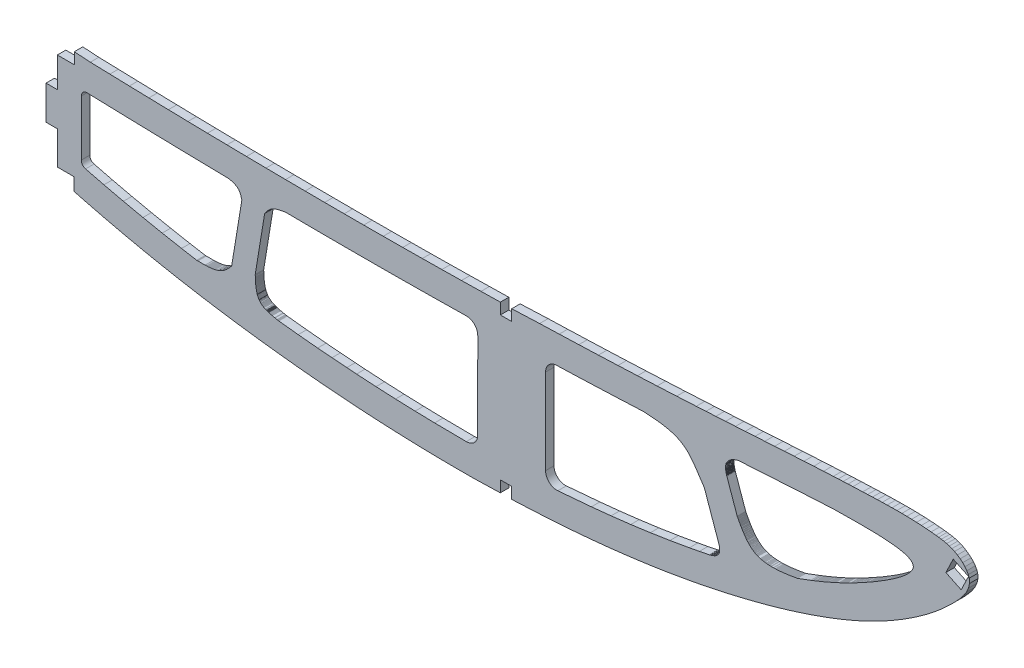
SolidWorks part; units mm, degrees
ref_plane "前视基准面" through (0, 0, 0) normal (0, 0, 1) x (1, 0, 0)
ref_plane "上视基准面" through (0, 0, 0) normal (0, 1, 0) x (1, 0, 0)
ref_plane "右视基准面" through (0, 0, 0) normal (1, 0, 0) x (0, 0, -1)
sketch "Model" plane through (0, 0, 0) normal (0, 0, 1) x (1, 0, 0)
  line L0 (54.7163, 305.1744) -> (56.537, 304.693)
  line L1 (56.537, 304.693) -> (59.9668, 303.84)
  line L2 (59.9668, 303.84) -> (63.4097, 303.0365)
  line L3 (63.4097, 303.0365) -> (66.8649, 302.2844)
  line L4 (66.8649, 302.2844) -> (70.2738, 301.5955)
  line L5 (70.2738, 301.5955) -> (73.6909, 300.9552)
  line L6 (73.6909, 300.9552) -> (77.1161, 300.3627)
  line L7 (77.1161, 300.3627) -> (80.5494, 299.8168)
  line L8 (80.5494, 299.8168) -> (83.9897, 299.3157)
  line L9 (83.9897, 299.3157) -> (87.4368, 298.8573)
  line L10 (87.4368, 298.8573) -> (90.8898, 298.4407)
  line L11 (90.8898, 298.4407) -> (94.3267, 298.0678)
  line L12 (94.3267, 298.0678) -> (97.7653, 297.7339)
  line L13 (97.7653, 297.7339) -> (101.2088, 297.4419)
  line L14 (101.2088, 297.4419) -> (104.6541, 297.1908)
  line L15 (104.6541, 297.1908) -> (108.1022, 296.9816)
  line L16 (108.1022, 296.9816) -> (111.5533, 296.8153)
  line L17 (111.5533, 296.8153) -> (115.0071, 296.6909)
  line L18 (115.0071, 296.6909) -> (118.4669, 296.6093)
  line L19 (118.4669, 296.6093) -> (121.9276, 296.5718)
  line L20 (121.9276, 296.5718) -> (125.3862, 296.5783)
  line L21 (125.3862, 296.5783) -> (130.0889, 296.7074)
  line L22 (132.0889, 296.7065) -> (135.7616, 296.8783)
  line L23 (135.7616, 296.8783) -> (139.2186, 297.0751)
  line L24 (139.2186, 297.0751) -> (142.7139, 297.3232)
  line L25 (142.7139, 297.3232) -> (146.2036, 297.6247)
  line L26 (146.2036, 297.6247) -> (149.6878, 297.9825)
  line L27 (149.6878, 297.9825) -> (153.1644, 298.3966)
  line L28 (153.1644, 298.3966) -> (156.6337, 298.8722)
  line L29 (156.6337, 298.8722) -> (160.0928, 299.4102)
  line L30 (160.0928, 299.4102) -> (163.5428, 300.0137)
  line L31 (163.5428, 300.0137) -> (165.3002, 300.3476)
  line L32 (165.3002, 300.3476) -> (167.0534, 300.6997)
  line L33 (167.0534, 300.6997) -> (168.8034, 301.0699)
  line L34 (168.8034, 301.0699) -> (170.5493, 301.4583)
  line L35 (170.5493, 301.4583) -> (172.2899, 301.865)
  line L36 (172.2899, 301.865) -> (174.0273, 302.2908)
  line L37 (174.0273, 302.2908) -> (175.7606, 302.7358)
  line L38 (175.7606, 302.7358) -> (177.5343, 303.2121)
  line L39 (177.5343, 303.2121) -> (179.302, 303.7107)
  line L40 (179.302, 303.7107) -> (181.0627, 304.2316)
  line L41 (181.0627, 304.2316) -> (182.8165, 304.7778)
  line L42 (182.8165, 304.7778) -> (184.5623, 305.3484)
  line L43 (184.5623, 305.3484) -> (186.2994, 305.9474)
  line L44 (186.2994, 305.9474) -> (188.0268, 306.5749)
  line L45 (188.0268, 306.5749) -> (188.9195, 306.9129)
  line L46 (188.9195, 306.9129) -> (189.8086, 307.258)
  line L47 (189.8086, 307.258) -> (190.6931, 307.6124)
  line L48 (190.6931, 307.6124) -> (191.574, 307.9769)
  line L49 (191.574, 307.9769) -> (192.4513, 308.3506)
  line L50 (192.4513, 308.3506) -> (193.3221, 308.7346)
  line L51 (193.3221, 308.7346) -> (194.1883, 309.1288)
  line L52 (194.1883, 309.1288) -> (195.09, 309.5544)
  line L53 (195.09, 309.5544) -> (195.9861, 309.9924)
  line L54 (195.9861, 309.9924) -> (196.8759, 310.4446)
  line L55 (196.8759, 310.4446) -> (197.7593, 310.9091)
  line L56 (197.7593, 310.9091) -> (198.6382, 311.3878)
  line L57 (198.6382, 311.3878) -> (199.5118, 311.8808)
  line L58 (199.5118, 311.8808) -> (200.3811, 312.39)
  line L59 (200.3811, 312.39) -> (201.314, 312.9564)
  line L60 (201.314, 312.9564) -> (202.2386, 313.5402)
  line L61 (202.2386, 313.5402) -> (203.1519, 314.1385)
  line L62 (203.1519, 314.1385) -> (204.0498, 314.7515)
  line L63 (204.0498, 314.7515) -> (204.9293, 315.3784)
  line L64 (204.9293, 315.3784) -> (205.7862, 316.0162)
  line L65 (205.7862, 316.0162) -> (206.6176, 316.6652)
  line L66 (206.6176, 316.6652) -> (207.1159, 317.0696)
  line L67 (207.1159, 317.0696) -> (207.6065, 317.4804)
  line L68 (207.6065, 317.4804) -> (208.0936, 317.9024)
  line L69 (208.0936, 317.9024) -> (208.5812, 318.3373)
  line L70 (208.5812, 318.3373) -> (209.0717, 318.7911)
  line L71 (209.0717, 318.7911) -> (209.5711, 319.2656)
  line L72 (209.5711, 319.2656) -> (210.0816, 319.7635)
  line L73 (210.0816, 319.7635) -> (210.7669, 320.46)
  line L74 (210.7669, 320.46) -> (211.4359, 321.1942)
  line L75 (211.4359, 321.1942) -> (212.0452, 321.9571)
  line L76 (212.0452, 321.9571) -> (212.5531, 322.7395)
  line L77 (212.5531, 322.7395) -> (212.9164, 323.5313)
  line L78 (212.9164, 323.5313) -> (213.0925, 324.3233)
  line L79 (213.0925, 324.3233) -> (213.0389, 325.1064)
  line L80 (213.0389, 325.1064) -> (212.8739, 325.5851)
  line L81 (212.8739, 325.5851) -> (212.6161, 326.0499)
  line L82 (212.6161, 326.0499) -> (212.5637, 326.1193)
  line L83 (212.5637, 326.1193) -> (212.2813, 326.4931)
  line L84 (212.2813, 326.4931) -> (211.8812, 326.9072)
  line L85 (211.8812, 326.9072) -> (211.4324, 327.2853)
  line L86 (211.4324, 327.2853) -> (210.9467, 327.621)
  line L87 (210.9467, 327.621) -> (210.4408, 327.9066)
  line L88 (210.4408, 327.9066) -> (209.9825, 328.114)
  line L89 (209.9825, 328.114) -> (209.5195, 328.2826)
  line L90 (209.5195, 328.2826) -> (209.052, 328.4183)
  line L91 (209.052, 328.4183) -> (208.5803, 328.5252)
  line L92 (208.5803, 328.5252) -> (208.1066, 328.6102)
  line L93 (208.1066, 328.6102) -> (207.6291, 328.6783)
  line L94 (207.6291, 328.6783) -> (207.1502, 328.7365)
  line L95 (207.1502, 328.7365) -> (206.2944, 328.8263)
  line L96 (206.2944, 328.8263) -> (205.4358, 328.9002)
  line L97 (205.4358, 328.9002) -> (204.5746, 328.9602)
  line L98 (204.5746, 328.9602) -> (203.7118, 329.0073)
  line L99 (203.7118, 329.0073) -> (202.8465, 329.0415)
  line L100 (202.8465, 329.0415) -> (201.9816, 329.0636)
  line L101 (201.9816, 329.0636) -> (201.1173, 329.0757)
  line L102 (201.1173, 329.0757) -> (200.2506, 329.0779)
  line L103 (200.2506, 329.0779) -> (199.3854, 329.0711)
  line L104 (199.3854, 329.0711) -> (198.5199, 329.0562)
  line L105 (198.5199, 329.0562) -> (197.6552, 329.0353)
  line L106 (197.6552, 329.0353) -> (196.7912, 329.0094)
  line L107 (196.7912, 329.0094) -> (195.9271, 328.9804)
  line L108 (195.9271, 328.9804) -> (195.0628, 328.9485)
  line L109 (195.0628, 328.9485) -> (194.1966, 328.9166)
  line L110 (194.1966, 328.9166) -> (193.3312, 328.8817)
  line L111 (193.3312, 328.8817) -> (192.4658, 328.8469)
  line L112 (192.4658, 328.8469) -> (191.5994, 328.81)
  line L113 (191.5994, 328.81) -> (190.7338, 328.7721)
  line L114 (190.7338, 328.7721) -> (189.8683, 328.7332)
  line L115 (189.8683, 328.7332) -> (189.0026, 328.6914)
  line L116 (189.0026, 328.6914) -> (187.2691, 328.6047)
  line L117 (187.2691, 328.6047) -> (185.5363, 328.511)
  line L118 (185.5363, 328.511) -> (183.8033, 328.4133)
  line L119 (183.8033, 328.4133) -> (182.0712, 328.3125)
  line L120 (182.0712, 328.3125) -> (180.3399, 328.2087)
  line L121 (180.3399, 328.2087) -> (178.6076, 328.104)
  line L122 (178.6076, 328.104) -> (176.8753, 327.9983)
  line L123 (176.8753, 327.9983) -> (175.142, 327.8946)
  line L124 (175.142, 327.8946) -> (173.4097, 327.7908)
  line L125 (173.4097, 327.7908) -> (171.6776, 327.6891)
  line L126 (171.6776, 327.6891) -> (169.9455, 327.5883)
  line L127 (169.9455, 327.5883) -> (168.2124, 327.4896)
  line L128 (168.2124, 327.4896) -> (166.4805, 327.3929)
  line L129 (166.4805, 327.3929) -> (164.7466, 327.2982)
  line L130 (164.7466, 327.2982) -> (161.2842, 327.1156)
  line L131 (161.2842, 327.1156) -> (157.8222, 326.9431)
  line L132 (157.8222, 326.9431) -> (154.3597, 326.7805)
  line L133 (154.3597, 326.7805) -> (150.8976, 326.627)
  line L134 (150.8976, 326.627) -> (147.4349, 326.4845)
  line L135 (147.4349, 326.4845) -> (143.9708, 326.3531)
  line L136 (143.9708, 326.3531) -> (140.5051, 326.2327)
  line L137 (140.5051, 326.2327) -> (137.0449, 326.1241)
  line L138 (137.0449, 326.1241) -> (133.1018, 325.9603)
  line L139 (130.1023, 325.9338) -> (126.6684, 325.8643)
  line L140 (126.6684, 325.8643) -> (123.2092, 325.8007)
  line L141 (123.2092, 325.8007) -> (119.7485, 325.7472)
  line L142 (119.7485, 325.7472) -> (116.2873, 325.7057)
  line L143 (116.2873, 325.7057) -> (112.8296, 325.6761)
  line L144 (112.8296, 325.6761) -> (109.3734, 325.6564)
  line L145 (109.3734, 325.6564) -> (105.9176, 325.6467)
  line L146 (105.9176, 325.6467) -> (102.4623, 325.648)
  line L147 (102.4623, 325.648) -> (99.0064, 325.6584)
  line L148 (99.0064, 325.6584) -> (95.5499, 325.6777)
  line L149 (95.5499, 325.6777) -> (92.0928, 325.7062)
  line L150 (92.0928, 325.7062) -> (88.6381, 325.7425)
  line L151 (88.6381, 325.7425) -> (85.1837, 325.7878)
  line L152 (85.1837, 325.7878) -> (81.7307, 325.84)
  line L153 (81.7307, 325.84) -> (78.277, 325.9013)
  line L154 (78.277, 325.9013) -> (74.8247, 325.9706)
  line L155 (74.8247, 325.9706) -> (71.3707, 326.0469)
  line L156 (71.3707, 326.0469) -> (67.917, 326.1302)
  line L157 (67.917, 326.1302) -> (64.4637, 326.2215)
  line L158 (64.4637, 326.2215) -> (61.0127, 326.3197)
  line L159 (61.0127, 326.3197) -> (57.5609, 326.423)
  line L160 (57.5609, 326.423) -> (54.7261, 326.6073)
  line L161 (189.0004, 323.6896) -> (187.2668, 323.6047)
  line L162 (187.2668, 323.6047) -> (185.534, 323.511)
  line L163 (185.534, 323.511) -> (183.801, 323.4133)
  line L164 (183.801, 323.4133) -> (182.9349, 323.3629)
  line L165 (181.7835, 323.2954) -> (180.3376, 323.2087)
  line L166 (180.3376, 323.2087) -> (178.6053, 323.104)
  line L167 (178.6053, 323.104) -> (176.873, 322.9983)
  line L168 (176.873, 322.9983) -> (175.1397, 322.8946)
  line L169 (175.1397, 322.8946) -> (173.4074, 322.7908)
  line L170 (173.4074, 322.7908) -> (172.14, 322.7173)
  line L171 (155.3496, 321.8251) -> (154.3574, 321.7805)
  line L172 (154.3574, 321.7805) -> (150.8953, 321.627)
  line L173 (150.8953, 321.627) -> (149.9596, 321.5885)
  line L174 (149.1639, 321.5557) -> (147.4326, 321.4845)
  line L175 (147.4326, 321.4845) -> (143.9685, 321.3531)
  line L176 (143.9685, 321.3531) -> (140.0298, 321.2163)
  line L177 (138.0993, 319.2184) -> (138.0923, 304.1049)
  line L178 (140.2644, 302.1114) -> (146.2059, 302.6247)
  line L179 (146.2059, 302.6247) -> (149.6901, 302.9825)
  line L180 (149.6901, 302.9825) -> (153.1667, 303.3966)
  line L181 (153.1667, 303.3966) -> (153.3969, 303.4282)
  line L182 (154.9014, 303.6344) -> (156.636, 303.8722)
  line L183 (156.636, 303.8722) -> (160.0951, 304.4102)
  line L184 (160.0951, 304.4102) -> (163.5451, 305.0137)
  line L185 (163.5451, 305.0137) -> (165.3025, 305.3476)
  line L186 (165.3025, 305.3476) -> (167.0522, 305.6997)
  line L187 (124.0682, 320.814) -> (119.7462, 320.7472)
  line L188 (119.7462, 320.7472) -> (116.285, 320.7057)
  line L189 (116.285, 320.7057) -> (112.8273, 320.6761)
  line L190 (112.8273, 320.6761) -> (109.3711, 320.6564)
  line L191 (109.3711, 320.6564) -> (105.9153, 320.6467)
  line L192 (105.9153, 320.6467) -> (102.46, 320.648)
  line L193 (100.8133, 320.653) -> (99.0041, 320.6584)
  line L194 (99.0041, 320.6584) -> (95.5476, 320.6777)
  line L195 (95.5476, 320.6777) -> (92.0905, 320.7062)
  line L196 (82.1046, 320.8344) -> (81.7283, 320.84)
  line L197 (81.7283, 320.84) -> (78.2747, 320.9013)
  line L198 (78.2747, 320.9013) -> (74.8224, 320.9706)
  line L199 (74.8224, 320.9706) -> (71.3684, 321.0469)
  line L200 (71.3684, 321.0469) -> (67.9147, 321.1302)
  line L201 (66.3216, 321.1723) -> (64.4614, 321.2215)
  line L202 (64.4614, 321.2215) -> (61.0104, 321.3197)
  line L203 (61.0104, 321.3197) -> (56.9977, 321.4398)
  line L204 (55.9678, 320.4407) -> (55.9633, 310.6185)
  line L205 (56.7219, 309.6476) -> (59.9691, 308.84)
  line L206 (59.9691, 308.84) -> (63.412, 308.0365)
  line L207 (63.412, 308.0365) -> (65.5693, 307.5669)
  line L208 (66.8672, 307.2844) -> (70.2761, 306.5955)
  line L209 (70.2761, 306.5955) -> (73.6932, 305.9552)
  line L210 (73.6932, 305.9552) -> (76.3894, 305.4888)
  line L211 (90.8921, 303.4407) -> (94.329, 303.0678)
  line L212 (94.329, 303.0678) -> (97.7676, 302.7339)
  line L213 (97.7676, 302.7339) -> (100.3081, 302.5185)
  line L214 (102.9338, 302.3163) -> (104.6564, 302.1908)
  line L215 (104.6564, 302.1908) -> (108.1045, 301.9816)
  line L216 (108.1045, 301.9816) -> (111.5556, 301.8153)
  line L217 (111.5556, 301.8153) -> (115.0094, 301.6909)
  line L218 (115.0094, 301.6909) -> (118.4692, 301.6093)
  line L219 (118.4692, 301.6093) -> (124.0703, 301.5485)
  line L220 (126.092, 303.5475) -> (126.0991, 318.8133)
  line L221 (212.9144, 325.3174) -> (211.6183, 322.6119)
  line L222 (211.6183, 322.6119) -> (208.9127, 323.908)
  line L223 (208.9127, 323.908) -> (210.2089, 326.6135)
  line L224 (210.2089, 326.6135) -> (212.9144, 325.3174)
  line L225 (132.0898, 298.7065) -> (130.0898, 298.7074)
  line L226 (51.7173, 307.4357) -> (54.7173, 307.4343)
  line L227 (54.7173, 307.4343) -> (54.7163, 305.1744)
  line L228 (51.7173, 307.4357) -> (51.72, 313.2988)
  line L229 (51.7228, 319.2988) -> (51.7252, 324.6087)
  line L230 (54.7261, 326.6073) -> (54.7252, 324.6073)
  line L231 (54.7252, 324.6073) -> (51.7252, 324.6087)
  line L232 (51.72, 313.2988) -> (49.72, 313.2997)
  line L233 (49.72, 313.2997) -> (49.7228, 319.2997)
  line L234 (49.7228, 319.2997) -> (51.7228, 319.2988)
  line L235 (130.0898, 298.7074) -> (130.0889, 296.7074)
  line L236 (132.0898, 298.7065) -> (132.0889, 296.7065)
  line L237 (132.1014, 323.9607) -> (130.1014, 323.9617)
  line L238 (130.1014, 323.9617) -> (130.1023, 325.9338)
  line L239 (132.1014, 323.9607) -> (132.1023, 325.9187)
  line L240 (66.3216, 321.1723) -> (67.9147, 321.1302)
  line L241 (65.5693, 307.5669) -> (66.8672, 307.2844)
  line L242 (100.8133, 320.653) -> (102.46, 320.648)
  line L243 (100.3081, 302.5185) -> (102.9338, 302.3163)
  line L244 (149.1639, 321.5557) -> (149.9596, 321.5885)
  line L245 (153.3969, 303.4282) -> (154.9014, 303.6344)
  line L246 (181.7835, 323.2954) -> (182.9349, 323.3629)
  line L247 (182.6141, 309.8725) -> (185.0345, 310.7814)
  line L248 (84.3681, 318.7077) -> (82.5631, 307.6886)
  line L249 (86.7334, 308.4766) -> (88.3981, 318.6559)
  line L250 (166.1767, 315.5501) -> (168.7933, 308.1089)
  line L251 (170.1584, 319.3082) -> (171.996, 314.0774)
  line L252 (133.1018, 325.9603) -> (132.1023, 325.9187)
  line L253 (185.0345, 310.7814) -> (185.1945, 310.8413)
  line L254 (185.1945, 310.8413) -> (185.3546, 310.9013)
  line L255 (185.3546, 310.9013) -> (185.5146, 310.9712)
  line L256 (185.5146, 310.9712) -> (185.6746, 311.0311)
  line L257 (185.6746, 311.0311) -> (185.8346, 311.091)
  line L258 (185.8346, 311.091) -> (185.9947, 311.161)
  line L259 (185.9947, 311.161) -> (186.1547, 311.2209)
  line L260 (186.1547, 311.2209) -> (186.3247, 311.2908)
  line L261 (186.3247, 311.2908) -> (186.4848, 311.3607)
  line L262 (186.4848, 311.3607) -> (186.6448, 311.4207)
  line L263 (186.6448, 311.4207) -> (186.8048, 311.4906)
  line L264 (186.8048, 311.4906) -> (186.9749, 311.5605)
  line L265 (186.9749, 311.5605) -> (187.1349, 311.6304)
  line L266 (187.1349, 311.6304) -> (187.3049, 311.6904)
  line L267 (187.3049, 311.6904) -> (187.4649, 311.7603)
  line L268 (187.4649, 311.7603) -> (187.635, 311.8302)
  line L269 (187.635, 311.8302) -> (187.795, 311.9101)
  line L270 (187.795, 311.9101) -> (187.9651, 311.9801)
  line L271 (187.9651, 311.9801) -> (188.1351, 312.05)
  line L272 (188.1351, 312.05) -> (188.2951, 312.1199)
  line L273 (188.2951, 312.1199) -> (188.4652, 312.1998)
  line L274 (188.4652, 312.1998) -> (188.6352, 312.2697)
  line L275 (188.6352, 312.2697) -> (188.8052, 312.3497)
  line L276 (188.8052, 312.3497) -> (188.9753, 312.4196)
  line L277 (188.9753, 312.4196) -> (189.1453, 312.4995)
  line L278 (189.1453, 312.4995) -> (189.3153, 312.5694)
  line L279 (189.3153, 312.5694) -> (189.4854, 312.6494)
  line L280 (189.4854, 312.6494) -> (189.6554, 312.7293)
  line L281 (189.6554, 312.7293) -> (189.8254, 312.8092)
  line L282 (189.8254, 312.8092) -> (189.9955, 312.8891)
  line L283 (189.9955, 312.8891) -> (190.1755, 312.969)
  line L284 (190.1755, 312.969) -> (190.3455, 313.049)
  line L285 (190.3455, 313.049) -> (190.5156, 313.1389)
  line L286 (190.5156, 313.1389) -> (190.6956, 313.2188)
  line L287 (190.6956, 313.2188) -> (190.8657, 313.3087)
  line L288 (190.8657, 313.3087) -> (191.0457, 313.3886)
  line L289 (191.0457, 313.3886) -> (191.2257, 313.4786)
  line L290 (191.2257, 313.4786) -> (191.3958, 313.5585)
  line L291 (191.3958, 313.5585) -> (191.5758, 313.6484)
  line L292 (191.5758, 313.6484) -> (191.7559, 313.7383)
  line L293 (191.7559, 313.7383) -> (191.9359, 313.8282)
  line L294 (191.9359, 313.8282) -> (192.1159, 313.9181)
  line L295 (192.1159, 313.9181) -> (192.296, 314.0181)
  line L296 (192.296, 314.0181) -> (192.476, 314.108)
  line L297 (192.476, 314.108) -> (192.6561, 314.1979)
  line L298 (192.6561, 314.1979) -> (192.8361, 314.2978)
  line L299 (192.8361, 314.2978) -> (193.0262, 314.3877)
  line L300 (193.0262, 314.3877) -> (193.2062, 314.4876)
  line L301 (193.2062, 314.4876) -> (193.3863, 314.5876)
  line L302 (193.3863, 314.5876) -> (193.5763, 314.6875)
  line L303 (193.5763, 314.6875) -> (193.7663, 314.7874)
  line L304 (193.7663, 314.7874) -> (193.9464, 314.8873)
  line L305 (193.9464, 314.8873) -> (194.1364, 314.9872)
  line L306 (194.1364, 314.9872) -> (194.3265, 315.0871)
  line L307 (194.3265, 315.0871) -> (194.5165, 315.197)
  line L308 (194.5165, 315.197) -> (194.7066, 315.297)
  line L309 (194.7066, 315.297) -> (194.8966, 315.4069)
  line L310 (194.8966, 315.4069) -> (195.0867, 315.5168)
  line L311 (195.0867, 315.5168) -> (195.2767, 315.6267)
  line L312 (195.2767, 315.6267) -> (195.4768, 315.7366)
  line L313 (195.4768, 315.7366) -> (195.6668, 315.8465)
  line L314 (195.6668, 315.8465) -> (195.8569, 315.9564)
  line L315 (195.8569, 315.9564) -> (196.0569, 316.0663)
  line L316 (196.0569, 316.0663) -> (196.257, 316.1862)
  line L317 (196.257, 316.1862) -> (196.447, 316.3062)
  line L318 (196.447, 316.3062) -> (196.6471, 316.4161)
  line L319 (196.6471, 316.4161) -> (196.8471, 316.536)
  line L320 (196.8471, 316.536) -> (197.0372, 316.6559)
  line L321 (197.0372, 316.6559) -> (197.2373, 316.7758)
  line L322 (197.2373, 316.7758) -> (197.4273, 316.8957)
  line L323 (197.4273, 316.8957) -> (197.6274, 317.0156)
  line L324 (197.6274, 317.0156) -> (197.8274, 317.1355)
  line L325 (197.8274, 317.1355) -> (198.0175, 317.2554)
  line L326 (198.0175, 317.2554) -> (198.2075, 317.3753)
  line L327 (198.2075, 317.3753) -> (198.3976, 317.4953)
  line L328 (198.3976, 317.4953) -> (198.5876, 317.6252)
  line L329 (198.5876, 317.6252) -> (198.7777, 317.7451)
  line L330 (198.7777, 317.7451) -> (198.9678, 317.865)
  line L331 (198.9678, 317.865) -> (199.1478, 317.9949)
  line L332 (199.1478, 317.9949) -> (199.3379, 318.1148)
  line L333 (199.3379, 318.1148) -> (199.5179, 318.2347)
  line L334 (199.5179, 318.2347) -> (199.688, 318.3547)
  line L335 (199.688, 318.3547) -> (199.868, 318.4846)
  line L336 (199.868, 318.4846) -> (200.0381, 318.6045)
  line L337 (200.0381, 318.6045) -> (200.2082, 318.7244)
  line L338 (200.2082, 318.7244) -> (200.3782, 318.8443)
  line L339 (200.3782, 318.8443) -> (200.5383, 318.9643)
  line L340 (200.5383, 318.9643) -> (200.6983, 319.0942)
  line L341 (200.6983, 319.0942) -> (200.8584, 319.2141)
  line L342 (200.8584, 319.2141) -> (201.0084, 319.3241)
  line L343 (201.0084, 319.3241) -> (201.1585, 319.444)
  line L344 (201.1585, 319.444) -> (201.3085, 319.5639)
  line L345 (201.3085, 319.5639) -> (201.4486, 319.6838)
  line L346 (201.4486, 319.6838) -> (201.5786, 319.7938)
  line L347 (201.5786, 319.7938) -> (201.7187, 319.9137)
  line L348 (201.7187, 319.9137) -> (201.8388, 320.0237)
  line L349 (201.8388, 320.0237) -> (201.9688, 320.1436)
  line L350 (201.9688, 320.1436) -> (202.0789, 320.2536)
  line L351 (202.0789, 320.2536) -> (202.1989, 320.3635)
  line L352 (202.1989, 320.3635) -> (202.299, 320.4735)
  line L353 (202.299, 320.4735) -> (202.399, 320.5734)
  line L354 (202.399, 320.5734) -> (202.4991, 320.6834)
  line L355 (202.4991, 320.6834) -> (202.5891, 320.7933)
  line L356 (202.5891, 320.7933) -> (202.6692, 320.8933)
  line L357 (202.6692, 320.8933) -> (202.7492, 320.9933)
  line L358 (202.7492, 320.9933) -> (202.8192, 321.0932)
  line L359 (202.8192, 321.0932) -> (202.8793, 321.1932)
  line L360 (202.8793, 321.1932) -> (202.9393, 321.2832)
  line L361 (202.9393, 321.2832) -> (202.9894, 321.3831)
  line L362 (202.9894, 321.3831) -> (203.0394, 321.4731)
  line L363 (203.0394, 321.4731) -> (203.0695, 321.5631)
  line L364 (203.0695, 321.5631) -> (203.0995, 321.6531)
  line L365 (203.0995, 321.6531) -> (203.1295, 321.7331)
  line L366 (203.1295, 321.7331) -> (203.1396, 321.8131)
  line L367 (203.1396, 321.8131) -> (203.1496, 321.9031)
  line L368 (203.1496, 321.9031) -> (203.1497, 321.9731)
  line L369 (203.1497, 321.9731) -> (203.1397, 322.0531)
  line L370 (203.1397, 322.0531) -> (203.1197, 322.1331)
  line L371 (203.1197, 322.1331) -> (203.0998, 322.2031)
  line L372 (203.0998, 322.2031) -> (203.0698, 322.2731)
  line L373 (203.0698, 322.2731) -> (203.0298, 322.3431)
  line L374 (203.0298, 322.3431) -> (202.9898, 322.4031)
  line L375 (202.9898, 322.4031) -> (202.9399, 322.4732)
  line L376 (202.9399, 322.4732) -> (202.8799, 322.5332)
  line L377 (202.8799, 322.5332) -> (202.8199, 322.5932)
  line L378 (202.8199, 322.5932) -> (202.75, 322.6533)
  line L379 (202.75, 322.6533) -> (202.67, 322.7033)
  line L380 (202.67, 322.7033) -> (202.59, 322.7633)
  line L381 (202.59, 322.7633) -> (202.5, 322.8134)
  line L382 (202.5, 322.8134) -> (202.4101, 322.8634)
  line L383 (202.4101, 322.8634) -> (202.3101, 322.9135)
  line L384 (202.3101, 322.9135) -> (202.2001, 322.9635)
  line L385 (202.2001, 322.9635) -> (202.0901, 323.0036)
  line L386 (202.0901, 323.0036) -> (201.9701, 323.0436)
  line L387 (201.9701, 323.0436) -> (201.8402, 323.0937)
  line L388 (201.8402, 323.0937) -> (201.7102, 323.1337)
  line L389 (201.7102, 323.1337) -> (201.5802, 323.1738)
  line L390 (201.5802, 323.1738) -> (201.4402, 323.2039)
  line L391 (201.4402, 323.2039) -> (201.2902, 323.2439)
  line L392 (201.2902, 323.2439) -> (201.1402, 323.274)
  line L393 (201.1402, 323.274) -> (200.9903, 323.3141)
  line L394 (200.9903, 323.3141) -> (200.8303, 323.3441)
  line L395 (200.8303, 323.3441) -> (200.6603, 323.3742)
  line L396 (200.6603, 323.3742) -> (200.4903, 323.3943)
  line L397 (200.4903, 323.3943) -> (200.3203, 323.4244)
  line L398 (200.3203, 323.4244) -> (200.1403, 323.4545)
  line L399 (200.1403, 323.4545) -> (199.9603, 323.4745)
  line L400 (199.9603, 323.4745) -> (199.7704, 323.4946)
  line L401 (199.7704, 323.4946) -> (199.5804, 323.5247)
  line L402 (199.5804, 323.5247) -> (199.3804, 323.5448)
  line L403 (199.3804, 323.5448) -> (199.1804, 323.5649)
  line L404 (199.1804, 323.5649) -> (198.9804, 323.575)
  line L405 (198.9804, 323.575) -> (198.7704, 323.5951)
  line L406 (198.7704, 323.5951) -> (198.5604, 323.6152)
  line L407 (198.5604, 323.6152) -> (198.3404, 323.6253)
  line L408 (198.3404, 323.6253) -> (198.1204, 323.6454)
  line L409 (198.1204, 323.6454) -> (197.9004, 323.6555)
  line L410 (197.9004, 323.6555) -> (197.6704, 323.6656)
  line L411 (197.6704, 323.6656) -> (197.4504, 323.6757)
  line L412 (197.4504, 323.6757) -> (197.2104, 323.6858)
  line L413 (197.2104, 323.6858) -> (196.9804, 323.6959)
  line L414 (196.9804, 323.6959) -> (196.7404, 323.706)
  line L415 (196.7404, 323.706) -> (196.5004, 323.7061)
  line L416 (196.5004, 323.7061) -> (196.2605, 323.7162)
  line L417 (196.2605, 323.7162) -> (196.0105, 323.7264)
  line L418 (196.0105, 323.7264) -> (195.7605, 323.7265)
  line L419 (195.7605, 323.7265) -> (195.5105, 323.7366)
  line L420 (195.5105, 323.7366) -> (195.2605, 323.7367)
  line L421 (195.2605, 323.7367) -> (195.0005, 323.7368)
  line L422 (195.0005, 323.7368) -> (194.7405, 323.7369)
  line L423 (194.7405, 323.7369) -> (194.4805, 323.7471)
  line L424 (194.4805, 323.7471) -> (194.2205, 323.7472)
  line L425 (194.2205, 323.7472) -> (193.9605, 323.7473)
  line L426 (193.9605, 323.7473) -> (193.6905, 323.7474)
  line L427 (193.6905, 323.7474) -> (193.4205, 323.7475)
  line L428 (193.4205, 323.7475) -> (193.1505, 323.7477)
  line L429 (193.1505, 323.7477) -> (192.8805, 323.7378)
  line L430 (192.8805, 323.7378) -> (192.6105, 323.7379)
  line L431 (192.6105, 323.7379) -> (192.3405, 323.738)
  line L432 (192.3405, 323.738) -> (192.0705, 323.7382)
  line L433 (192.0705, 323.7382) -> (191.7905, 323.7283)
  line L434 (191.7905, 323.7283) -> (191.5105, 323.7284)
  line L435 (191.5105, 323.7284) -> (191.2405, 323.7285)
  line L436 (191.2405, 323.7285) -> (190.9605, 323.7187)
  line L437 (190.9605, 323.7187) -> (190.6805, 323.7188)
  line L438 (190.6805, 323.7188) -> (190.4004, 323.7089)
  line L439 (190.4004, 323.7089) -> (190.1204, 323.7091)
  line L440 (190.1204, 323.7091) -> (189.8404, 323.7092)
  line L441 (189.8404, 323.7092) -> (189.5604, 323.6993)
  line L442 (189.5604, 323.6993) -> (189.2804, 323.6994)
  line L443 (189.2804, 323.6994) -> (189.0004, 323.6896)
  line L444 (182.6141, 309.8725) -> (182.5441, 309.8625)
  line L445 (182.5441, 309.8625) -> (182.4841, 309.8526)
  line L446 (182.4841, 309.8526) -> (182.4141, 309.8426)
  line L447 (182.4141, 309.8426) -> (182.3541, 309.8326)
  line L448 (182.3541, 309.8326) -> (182.2941, 309.8227)
  line L449 (182.2941, 309.8227) -> (182.2241, 309.8127)
  line L450 (182.2241, 309.8127) -> (182.164, 309.8027)
  line L451 (182.164, 309.8027) -> (182.094, 309.7928)
  line L452 (182.094, 309.7928) -> (182.034, 309.7828)
  line L453 (182.034, 309.7828) -> (181.964, 309.7728)
  line L454 (181.964, 309.7728) -> (181.904, 309.7628)
  line L455 (181.904, 309.7628) -> (181.834, 309.7429)
  line L456 (181.834, 309.7429) -> (181.774, 309.7329)
  line L457 (181.774, 309.7329) -> (181.704, 309.7229)
  line L458 (181.704, 309.7229) -> (181.644, 309.713)
  line L459 (181.644, 309.713) -> (181.574, 309.703)
  line L460 (181.574, 309.703) -> (181.514, 309.693)
  line L461 (181.514, 309.693) -> (181.444, 309.6831)
  line L462 (181.444, 309.6831) -> (181.384, 309.6731)
  line L463 (181.384, 309.6731) -> (181.314, 309.6631)
  line L464 (181.314, 309.6631) -> (181.254, 309.6531)
  line L465 (181.254, 309.6531) -> (181.184, 309.6432)
  line L466 (181.184, 309.6432) -> (181.124, 309.6332)
  line L467 (181.124, 309.6332) -> (181.054, 309.6232)
  line L468 (181.054, 309.6232) -> (180.994, 309.6133)
  line L469 (180.994, 309.6133) -> (180.924, 309.6033)
  line L470 (180.924, 309.6033) -> (180.864, 309.6033)
  line L471 (180.864, 309.6033) -> (180.794, 309.5934)
  line L472 (180.794, 309.5934) -> (180.7339, 309.5834)
  line L473 (180.7339, 309.5834) -> (180.6639, 309.5734)
  line L474 (180.6639, 309.5734) -> (180.5939, 309.5634)
  line L475 (180.5939, 309.5634) -> (180.5339, 309.5535)
  line L476 (180.5339, 309.5535) -> (180.4639, 309.5435)
  line L477 (180.4639, 309.5435) -> (180.4039, 309.5335)
  line L478 (180.4039, 309.5335) -> (180.3339, 309.5336)
  line L479 (180.3339, 309.5336) -> (180.2639, 309.5236)
  line L480 (180.2639, 309.5236) -> (180.2039, 309.5136)
  line L481 (180.2039, 309.5136) -> (180.1339, 309.5037)
  line L482 (180.1339, 309.5037) -> (180.0739, 309.5037)
  line L483 (180.0739, 309.5037) -> (180.0039, 309.4937)
  line L484 (180.0039, 309.4937) -> (179.9339, 309.4837)
  line L485 (179.9339, 309.4837) -> (179.8739, 309.4738)
  line L486 (179.8739, 309.4738) -> (179.8039, 309.4738)
  line L487 (179.8039, 309.4738) -> (179.7339, 309.4638)
  line L488 (179.7339, 309.4638) -> (179.6739, 309.4639)
  line L489 (179.6739, 309.4639) -> (179.6039, 309.4539)
  line L490 (179.6039, 309.4539) -> (179.5339, 309.4439)
  line L491 (179.5339, 309.4439) -> (179.4639, 309.444)
  line L492 (179.4639, 309.444) -> (179.4039, 309.434)
  line L493 (179.4039, 309.434) -> (179.3339, 309.434)
  line L494 (179.3339, 309.434) -> (179.2639, 309.4241)
  line L495 (179.2639, 309.4241) -> (179.1939, 309.4241)
  line L496 (179.1939, 309.4241) -> (179.1339, 309.4141)
  line L497 (179.1339, 309.4141) -> (179.0639, 309.4141)
  line L498 (179.0639, 309.4141) -> (178.9939, 309.4142)
  line L499 (178.9939, 309.4142) -> (178.9239, 309.4042)
  line L500 (178.9239, 309.4042) -> (178.8539, 309.4042)
  line L501 (178.8539, 309.4042) -> (178.7839, 309.4043)
  line L502 (178.7839, 309.4043) -> (178.7139, 309.3943)
  line L503 (178.7139, 309.3943) -> (178.6539, 309.3943)
  line L504 (178.6539, 309.3943) -> (178.5839, 309.3944)
  line L505 (178.5839, 309.3944) -> (178.5139, 309.3944)
  line L506 (178.5139, 309.3944) -> (178.4439, 309.3944)
  line L507 (178.4439, 309.3944) -> (178.3739, 309.3845)
  line L508 (178.3739, 309.3845) -> (178.3039, 309.3845)
  line L509 (178.3039, 309.3845) -> (178.2339, 309.3845)
  line L510 (178.2339, 309.3845) -> (178.1639, 309.3846)
  line L511 (178.1639, 309.3846) -> (178.0939, 309.3846)
  line L512 (178.0939, 309.3846) -> (178.0239, 309.3846)
  line L513 (178.0239, 309.3846) -> (177.9539, 309.3947)
  line L514 (177.9539, 309.3947) -> (177.8939, 309.3947)
  line L515 (177.8939, 309.3947) -> (177.8239, 309.3947)
  line L516 (177.8239, 309.3947) -> (177.7539, 309.3948)
  line L517 (177.7539, 309.3948) -> (177.6839, 309.3948)
  line L518 (177.6839, 309.3948) -> (177.6139, 309.4048)
  line L519 (177.6139, 309.4048) -> (177.5439, 309.4048)
  line L520 (177.5439, 309.4048) -> (177.4739, 309.4149)
  line L521 (177.4739, 309.4149) -> (177.4039, 309.4149)
  line L522 (177.4039, 309.4149) -> (177.3439, 309.4249)
  line L523 (177.3439, 309.4249) -> (177.2739, 309.425)
  line L524 (177.2739, 309.425) -> (177.2039, 309.435)
  line L525 (177.2039, 309.435) -> (177.1339, 309.445)
  line L526 (177.1339, 309.445) -> (177.0739, 309.4451)
  line L527 (177.0739, 309.4451) -> (177.0039, 309.4551)
  line L528 (177.0039, 309.4551) -> (176.9339, 309.4651)
  line L529 (176.9339, 309.4651) -> (176.8639, 309.4752)
  line L530 (176.8639, 309.4752) -> (176.8039, 309.4852)
  line L531 (176.8039, 309.4852) -> (176.7339, 309.4952)
  line L532 (176.7339, 309.4952) -> (176.6739, 309.5052)
  line L533 (176.6739, 309.5052) -> (176.6039, 309.5153)
  line L534 (176.6039, 309.5153) -> (176.5339, 309.5353)
  line L535 (176.5339, 309.5353) -> (176.4739, 309.5453)
  line L536 (176.4739, 309.5453) -> (176.4039, 309.5554)
  line L537 (176.4039, 309.5554) -> (176.3439, 309.5754)
  line L538 (176.3439, 309.5754) -> (176.2839, 309.5854)
  line L539 (176.2839, 309.5854) -> (176.214, 309.6055)
  line L540 (176.214, 309.6055) -> (176.154, 309.6255)
  line L541 (176.154, 309.6255) -> (176.084, 309.6355)
  line L542 (176.084, 309.6355) -> (176.024, 309.6555)
  line L543 (176.024, 309.6555) -> (175.964, 309.6756)
  line L544 (175.964, 309.6756) -> (175.904, 309.6956)
  line L545 (175.904, 309.6956) -> (175.844, 309.7156)
  line L546 (175.844, 309.7156) -> (175.784, 309.7357)
  line L547 (175.784, 309.7357) -> (175.724, 309.7557)
  line L548 (175.724, 309.7557) -> (175.664, 309.7757)
  line L549 (175.664, 309.7757) -> (175.604, 309.8057)
  line L550 (175.604, 309.8057) -> (175.5441, 309.8258)
  line L551 (175.5441, 309.8258) -> (175.4841, 309.8558)
  line L552 (175.4841, 309.8558) -> (175.4241, 309.8758)
  line L553 (175.4241, 309.8758) -> (175.3641, 309.9059)
  line L554 (175.3641, 309.9059) -> (175.3141, 309.9359)
  line L555 (175.3141, 309.9359) -> (175.2541, 309.9659)
  line L556 (175.2541, 309.9659) -> (175.1941, 309.9959)
  line L557 (175.1941, 309.9959) -> (175.1441, 310.026)
  line L558 (175.1441, 310.026) -> (175.0842, 310.056)
  line L559 (175.0842, 310.056) -> (175.0342, 310.086)
  line L560 (175.0342, 310.086) -> (174.9842, 310.116)
  line L561 (174.9842, 310.116) -> (174.9242, 310.1561)
  line L562 (174.9242, 310.1561) -> (174.8742, 310.1861)
  line L563 (174.8742, 310.1861) -> (174.8242, 310.2261)
  line L564 (174.8242, 310.2261) -> (174.7743, 310.2561)
  line L565 (174.7743, 310.2561) -> (174.7243, 310.2961)
  line L566 (174.7243, 310.2961) -> (174.6643, 310.3362)
  line L567 (174.6643, 310.3362) -> (174.6143, 310.3662)
  line L568 (174.6143, 310.3662) -> (174.5743, 310.4062)
  line L569 (174.5743, 310.4062) -> (174.5243, 310.4462)
  line L570 (174.5243, 310.4462) -> (174.4744, 310.4863)
  line L571 (174.4744, 310.4863) -> (174.4244, 310.5363)
  line L572 (174.4244, 310.5363) -> (174.3744, 310.5763)
  line L573 (174.3744, 310.5763) -> (174.3244, 310.6163)
  line L574 (174.3244, 310.6163) -> (174.2844, 310.6563)
  line L575 (174.2844, 310.6563) -> (174.2345, 310.7064)
  line L576 (174.2345, 310.7064) -> (174.1845, 310.7464)
  line L577 (174.1845, 310.7464) -> (174.1445, 310.7964)
  line L578 (174.1445, 310.7964) -> (174.0945, 310.8364)
  line L579 (174.0945, 310.8364) -> (174.0545, 310.8865)
  line L580 (174.0545, 310.8865) -> (174.0046, 310.9365)
  line L581 (174.0046, 310.9365) -> (173.9646, 310.9765)
  line L582 (173.9646, 310.9765) -> (173.9246, 311.0265)
  line L583 (173.9246, 311.0265) -> (173.8746, 311.0765)
  line L584 (173.8746, 311.0765) -> (173.8347, 311.1266)
  line L585 (173.8347, 311.1266) -> (173.7947, 311.1766)
  line L586 (173.7947, 311.1766) -> (173.7547, 311.2266)
  line L587 (173.7547, 311.2266) -> (173.7047, 311.2766)
  line L588 (173.7047, 311.2766) -> (173.6647, 311.3266)
  line L589 (173.6647, 311.3266) -> (173.6248, 311.3867)
  line L590 (173.6248, 311.3867) -> (173.5848, 311.4367)
  line L591 (173.5848, 311.4367) -> (173.5448, 311.4867)
  line L592 (173.5448, 311.4867) -> (173.5048, 311.5467)
  line L593 (173.5048, 311.5467) -> (173.4649, 311.5967)
  line L594 (173.4649, 311.5967) -> (173.4249, 311.6467)
  line L595 (173.4249, 311.6467) -> (173.3849, 311.7068)
  line L596 (173.3849, 311.7068) -> (173.3449, 311.7568)
  line L597 (173.3449, 311.7568) -> (173.305, 311.8168)
  line L598 (173.305, 311.8168) -> (173.265, 311.8768)
  line L599 (173.265, 311.8768) -> (173.225, 311.9268)
  line L600 (173.225, 311.9268) -> (173.1951, 311.9868)
  line L601 (173.1951, 311.9868) -> (173.1551, 312.0469)
  line L602 (173.1551, 312.0469) -> (173.1151, 312.1069)
  line L603 (173.1151, 312.1069) -> (173.0751, 312.1569)
  line L604 (173.0751, 312.1569) -> (173.0452, 312.2169)
  line L605 (173.0452, 312.2169) -> (173.0052, 312.2769)
  line L606 (173.0052, 312.2769) -> (172.9652, 312.337)
  line L607 (172.9652, 312.337) -> (172.9352, 312.397)
  line L608 (172.9352, 312.397) -> (172.8953, 312.457)
  line L609 (172.8953, 312.457) -> (172.8553, 312.517)
  line L610 (172.8553, 312.517) -> (172.8253, 312.577)
  line L611 (172.8253, 312.577) -> (172.7854, 312.637)
  line L612 (172.7854, 312.637) -> (172.7554, 312.6971)
  line L613 (172.7554, 312.6971) -> (172.7154, 312.7571)
  line L614 (172.7154, 312.7571) -> (172.6754, 312.8171)
  line L615 (172.6754, 312.8171) -> (172.6455, 312.8771)
  line L616 (172.6455, 312.8771) -> (172.6055, 312.9471)
  line L617 (172.6055, 312.9471) -> (172.5755, 313.0071)
  line L618 (172.5755, 313.0071) -> (172.5355, 313.0672)
  line L619 (172.5355, 313.0672) -> (172.5056, 313.1272)
  line L620 (172.5056, 313.1272) -> (172.4756, 313.1872)
  line L621 (172.4756, 313.1872) -> (172.4356, 313.2572)
  line L622 (172.4356, 313.2572) -> (172.4057, 313.3172)
  line L623 (172.4057, 313.3172) -> (172.3657, 313.3772)
  line L624 (172.3657, 313.3772) -> (172.3357, 313.4472)
  line L625 (172.3357, 313.4472) -> (172.2958, 313.5073)
  line L626 (172.2958, 313.5073) -> (172.2658, 313.5673)
  line L627 (172.2658, 313.5673) -> (172.2258, 313.6373)
  line L628 (172.2258, 313.6373) -> (172.1958, 313.6973)
  line L629 (172.1958, 313.6973) -> (172.1659, 313.7573)
  line L630 (172.1659, 313.7573) -> (172.1259, 313.8273)
  line L631 (172.1259, 313.8273) -> (172.0959, 313.8874)
  line L632 (172.0959, 313.8874) -> (172.056, 313.9474)
  line L633 (172.056, 313.9474) -> (172.026, 314.0174)
  line L634 (172.026, 314.0174) -> (171.996, 314.0774)
  line L635 (167.0522, 305.6997) -> (167.0722, 305.6997)
  line L636 (167.0722, 305.6997) -> (167.0922, 305.7097)
  line L637 (167.0922, 305.7097) -> (167.1122, 305.7096)
  line L638 (167.1122, 305.7096) -> (167.1222, 305.7196)
  line L639 (167.1222, 305.7196) -> (167.1422, 305.7196)
  line L640 (167.1422, 305.7196) -> (167.1622, 305.7296)
  line L641 (167.1622, 305.7296) -> (167.1822, 305.7296)
  line L642 (167.1822, 305.7296) -> (167.2022, 305.7396)
  line L643 (167.2022, 305.7396) -> (167.2122, 305.7396)
  line L644 (167.2122, 305.7396) -> (167.2322, 305.7496)
  line L645 (167.2322, 305.7496) -> (167.2522, 305.7496)
  line L646 (167.2522, 305.7496) -> (167.2722, 305.7596)
  line L647 (167.2722, 305.7596) -> (167.2822, 305.7596)
  line L648 (167.2822, 305.7596) -> (167.3022, 305.7696)
  line L649 (167.3022, 305.7696) -> (167.3222, 305.7696)
  line L650 (167.3222, 305.7696) -> (167.3422, 305.7795)
  line L651 (167.3422, 305.7795) -> (167.3622, 305.7795)
  line L652 (167.3622, 305.7795) -> (167.3722, 305.7895)
  line L653 (167.3722, 305.7895) -> (167.3922, 305.7895)
  line L654 (167.3922, 305.7895) -> (167.4122, 305.7995)
  line L655 (167.4122, 305.7995) -> (167.4322, 305.7995)
  line L656 (167.4322, 305.7995) -> (167.4422, 305.8095)
  line L657 (167.4422, 305.8095) -> (167.4622, 305.8095)
  line L658 (167.4622, 305.8095) -> (167.4822, 305.8195)
  line L659 (167.4822, 305.8195) -> (167.5022, 305.8195)
  line L660 (167.5022, 305.8195) -> (167.5122, 305.8295)
  line L661 (167.5122, 305.8295) -> (167.5322, 305.8295)
  line L662 (167.5322, 305.8295) -> (167.5522, 305.8394)
  line L663 (167.5522, 305.8394) -> (167.5722, 305.8494)
  line L664 (167.5722, 305.8494) -> (167.5822, 305.8494)
  line L665 (167.5822, 305.8494) -> (167.6022, 305.8594)
  line L666 (167.6022, 305.8594) -> (167.6222, 305.8594)
  line L667 (167.6222, 305.8594) -> (167.6322, 305.8694)
  line L668 (167.6322, 305.8694) -> (167.6522, 305.8794)
  line L669 (167.6522, 305.8794) -> (167.6722, 305.8794)
  line L670 (167.6722, 305.8794) -> (167.6922, 305.8894)
  line L671 (167.6922, 305.8894) -> (167.7022, 305.8894)
  line L672 (167.7022, 305.8894) -> (167.7222, 305.8994)
  line L673 (167.7222, 305.8994) -> (167.7423, 305.9094)
  line L674 (167.7423, 305.9094) -> (167.7523, 305.9094)
  line L675 (167.7523, 305.9094) -> (167.7723, 305.9193)
  line L676 (167.7723, 305.9193) -> (167.7923, 305.9293)
  line L677 (167.7923, 305.9293) -> (167.8023, 305.9293)
  line L678 (167.8023, 305.9293) -> (167.8223, 305.9393)
  line L679 (167.8223, 305.9393) -> (167.8423, 305.9493)
  line L680 (167.8423, 305.9493) -> (167.8523, 305.9493)
  line L681 (167.8523, 305.9493) -> (167.8723, 305.9593)
  line L682 (167.8723, 305.9593) -> (167.8923, 305.9693)
  line L683 (167.8923, 305.9693) -> (167.9023, 305.9693)
  line L684 (167.9023, 305.9693) -> (167.9223, 305.9793)
  line L685 (167.9223, 305.9793) -> (167.9423, 305.9893)
  line L686 (167.9423, 305.9893) -> (167.9523, 305.9993)
  line L687 (167.9523, 305.9993) -> (167.9723, 305.9993)
  line L688 (167.9723, 305.9993) -> (167.9823, 306.0092)
  line L689 (167.9823, 306.0092) -> (168.0023, 306.0192)
  line L690 (168.0023, 306.0192) -> (168.0223, 306.0292)
  line L691 (168.0223, 306.0292) -> (168.0323, 306.0392)
  line L692 (168.0323, 306.0392) -> (168.0523, 306.0492)
  line L693 (168.0523, 306.0492) -> (168.0623, 306.0492)
  line L694 (168.0623, 306.0492) -> (168.0823, 306.0592)
  line L695 (168.0823, 306.0592) -> (168.0923, 306.0692)
  line L696 (168.0923, 306.0692) -> (168.1123, 306.0792)
  line L697 (168.1123, 306.0792) -> (168.1223, 306.0892)
  line L698 (168.1223, 306.0892) -> (168.1423, 306.0992)
  line L699 (168.1423, 306.0992) -> (168.1623, 306.1092)
  line L700 (168.1623, 306.1092) -> (168.1724, 306.1192)
  line L701 (168.1724, 306.1192) -> (168.1924, 306.1292)
  line L702 (168.1924, 306.1292) -> (168.2024, 306.1391)
  line L703 (168.2024, 306.1391) -> (168.2224, 306.1491)
  line L704 (168.2224, 306.1491) -> (168.2324, 306.1591)
  line L705 (168.2324, 306.1591) -> (168.2424, 306.1691)
  line L706 (168.2424, 306.1691) -> (168.2624, 306.1791)
  line L707 (168.2624, 306.1791) -> (168.2724, 306.1891)
  line L708 (168.2724, 306.1891) -> (168.2924, 306.1991)
  line L709 (168.2924, 306.1991) -> (168.3024, 306.2091)
  line L710 (168.3024, 306.2091) -> (168.3224, 306.2191)
  line L711 (168.3224, 306.2191) -> (168.3324, 306.2291)
  line L712 (168.3324, 306.2291) -> (168.3524, 306.2391)
  line L713 (168.3524, 306.2391) -> (168.3624, 306.2491)
  line L714 (168.3624, 306.2491) -> (168.3724, 306.2591)
  line L715 (168.3724, 306.2591) -> (168.3924, 306.2791)
  line L716 (168.3924, 306.2791) -> (168.4024, 306.2891)
  line L717 (168.4024, 306.2891) -> (168.4124, 306.299)
  line L718 (168.4124, 306.299) -> (168.4324, 306.309)
  line L719 (168.4324, 306.309) -> (168.4424, 306.319)
  line L720 (168.4424, 306.319) -> (168.4525, 306.339)
  line L721 (168.4525, 306.339) -> (168.4725, 306.349)
  line L722 (168.4725, 306.349) -> (168.4825, 306.359)
  line L723 (168.4825, 306.359) -> (168.4925, 306.379)
  line L724 (168.4925, 306.379) -> (168.5125, 306.389)
  line L725 (168.5125, 306.389) -> (168.5225, 306.399)
  line L726 (168.5225, 306.399) -> (168.5325, 306.419)
  line L727 (168.5325, 306.419) -> (168.5425, 306.429)
  line L728 (168.5425, 306.429) -> (168.5525, 306.439)
  line L729 (168.5525, 306.439) -> (168.5725, 306.459)
  line L730 (168.5725, 306.459) -> (168.5825, 306.469)
  line L731 (168.5825, 306.469) -> (168.5925, 306.489)
  line L732 (168.5925, 306.489) -> (168.6025, 306.499)
  line L733 (168.6025, 306.499) -> (168.6125, 306.509)
  line L734 (168.6125, 306.509) -> (168.6225, 306.529)
  line L735 (168.6225, 306.529) -> (168.6425, 306.5389)
  line L736 (168.6425, 306.5389) -> (168.6526, 306.5589)
  line L737 (168.6526, 306.5589) -> (168.6626, 306.5689)
  line L738 (168.6626, 306.5689) -> (168.6726, 306.5889)
  line L739 (168.6726, 306.5889) -> (168.6826, 306.5989)
  line L740 (168.6826, 306.5989) -> (168.6926, 306.6189)
  line L741 (168.6926, 306.6189) -> (168.7026, 306.6289)
  line L742 (168.7026, 306.6289) -> (168.7126, 306.6489)
  line L743 (168.7126, 306.6489) -> (168.7226, 306.6689)
  line L744 (168.7226, 306.6689) -> (168.7326, 306.6789)
  line L745 (168.7326, 306.6789) -> (168.7326, 306.6989)
  line L746 (168.7326, 306.6989) -> (168.7426, 306.7089)
  line L747 (168.7426, 306.7089) -> (168.7526, 306.7289)
  line L748 (168.7526, 306.7289) -> (168.7626, 306.7389)
  line L749 (168.7626, 306.7389) -> (168.7726, 306.7589)
  line L750 (168.7726, 306.7589) -> (168.7827, 306.7789)
  line L751 (168.7827, 306.7789) -> (168.7827, 306.7889)
  line L752 (168.7827, 306.7889) -> (168.7927, 306.8089)
  line L753 (168.7927, 306.8089) -> (168.8027, 306.8289)
  line L754 (168.8027, 306.8289) -> (168.8127, 306.8389)
  line L755 (168.8127, 306.8389) -> (168.8127, 306.8589)
  line L756 (168.8127, 306.8589) -> (168.8227, 306.8789)
  line L757 (168.8227, 306.8789) -> (168.8227, 306.8889)
  line L758 (168.8227, 306.8889) -> (168.8327, 306.9089)
  line L759 (168.8327, 306.9089) -> (168.8427, 306.9289)
  line L760 (168.8427, 306.9289) -> (168.8427, 306.9389)
  line L761 (168.8427, 306.9389) -> (168.8527, 306.9588)
  line L762 (168.8527, 306.9588) -> (168.8527, 306.9788)
  line L763 (168.8527, 306.9788) -> (168.8628, 306.9888)
  line L764 (168.8628, 306.9888) -> (168.8628, 307.0088)
  line L765 (168.8628, 307.0088) -> (168.8628, 307.0288)
  line L766 (168.8628, 307.0288) -> (168.8728, 307.0388)
  line L767 (168.8728, 307.0388) -> (168.8728, 307.0588)
  line L768 (168.8728, 307.0588) -> (168.8728, 307.0788)
  line L769 (168.8728, 307.0788) -> (168.8828, 307.0988)
  line L770 (168.8828, 307.0988) -> (168.8828, 307.1088)
  line L771 (168.8828, 307.1088) -> (168.8828, 307.1288)
  line L772 (168.8828, 307.1288) -> (168.8928, 307.1488)
  line L773 (168.8928, 307.1488) -> (168.8928, 307.1688)
  line L774 (168.8928, 307.1688) -> (168.8928, 307.1788)
  line L775 (168.8928, 307.1788) -> (168.8928, 307.1988)
  line L776 (168.8928, 307.1988) -> (168.8929, 307.2188)
  line L777 (168.8929, 307.2188) -> (168.8929, 307.2388)
  line L778 (168.8929, 307.2388) -> (168.9029, 307.2488)
  line L779 (168.9029, 307.2488) -> (168.9029, 307.2688)
  line L780 (168.9029, 307.2688) -> (168.9029, 307.2888)
  line L781 (168.9029, 307.2888) -> (168.9029, 307.3088)
  line L782 (168.9029, 307.3088) -> (168.9029, 307.3188)
  line L783 (168.9029, 307.3188) -> (168.9029, 307.3388)
  line L784 (168.9029, 307.3388) -> (168.9029, 307.3588)
  line L785 (168.9029, 307.3588) -> (168.9029, 307.3788)
  line L786 (168.9029, 307.3788) -> (168.9029, 307.3888)
  line L787 (168.9029, 307.3888) -> (168.9029, 307.4088)
  line L788 (168.9029, 307.4088) -> (168.903, 307.4288)
  line L789 (168.903, 307.4288) -> (168.893, 307.4488)
  line L790 (168.893, 307.4488) -> (168.893, 307.4688)
  line L791 (168.893, 307.4688) -> (168.893, 307.4788)
  line L792 (168.893, 307.4788) -> (168.893, 307.4988)
  line L793 (168.893, 307.4988) -> (168.893, 307.5188)
  line L794 (168.893, 307.5188) -> (168.893, 307.5388)
  line L795 (168.893, 307.5388) -> (168.893, 307.5588)
  line L796 (168.893, 307.5588) -> (168.883, 307.5688)
  line L797 (168.883, 307.5688) -> (168.883, 307.5888)
  line L798 (168.883, 307.5888) -> (168.883, 307.6088)
  line L799 (168.883, 307.6088) -> (168.883, 307.6288)
  line L800 (168.883, 307.6288) -> (168.8831, 307.6488)
  line L801 (168.8831, 307.6488) -> (168.8731, 307.6688)
  line L802 (168.8731, 307.6688) -> (168.8731, 307.6788)
  line L803 (168.8731, 307.6788) -> (168.8731, 307.6988)
  line L804 (168.8731, 307.6988) -> (168.8731, 307.7188)
  line L805 (168.8731, 307.7188) -> (168.8631, 307.7388)
  line L806 (168.8631, 307.7388) -> (168.8631, 307.7588)
  line L807 (168.8631, 307.7588) -> (168.8631, 307.7788)
  line L808 (168.8631, 307.7788) -> (168.8531, 307.7888)
  line L809 (168.8531, 307.7888) -> (168.8531, 307.8088)
  line L810 (168.8531, 307.8088) -> (168.8531, 307.8288)
  line L811 (168.8531, 307.8288) -> (168.8431, 307.8489)
  line L812 (168.8431, 307.8489) -> (168.8432, 307.8689)
  line L813 (168.8432, 307.8689) -> (168.8432, 307.8889)
  line L814 (168.8432, 307.8889) -> (168.8332, 307.8989)
  line L815 (168.8332, 307.8989) -> (168.8332, 307.9189)
  line L816 (168.8332, 307.9189) -> (168.8332, 307.9389)
  line L817 (168.8332, 307.9389) -> (168.8232, 307.9589)
  line L818 (168.8232, 307.9589) -> (168.8232, 307.9789)
  line L819 (168.8232, 307.9789) -> (168.8232, 307.9989)
  line L820 (168.8232, 307.9989) -> (168.8132, 308.0089)
  line L821 (168.8132, 308.0089) -> (168.8132, 308.0289)
  line L822 (168.8132, 308.0289) -> (168.8132, 308.0489)
  line L823 (168.8132, 308.0489) -> (168.8032, 308.0689)
  line L824 (168.8032, 308.0689) -> (168.8033, 308.0889)
  line L825 (168.8033, 308.0889) -> (168.7933, 308.1089)
  line L826 (170.1584, 319.3082) -> (170.1484, 319.3283)
  line L827 (170.1484, 319.3283) -> (170.1384, 319.3583)
  line L828 (170.1384, 319.3583) -> (170.1385, 319.3783)
  line L829 (170.1385, 319.3783) -> (170.1285, 319.4083)
  line L830 (170.1285, 319.4083) -> (170.1185, 319.4283)
  line L831 (170.1185, 319.4283) -> (170.1185, 319.4583)
  line L832 (170.1185, 319.4583) -> (170.1085, 319.4783)
  line L833 (170.1085, 319.4783) -> (170.0985, 319.4983)
  line L834 (170.0985, 319.4983) -> (170.0985, 319.5283)
  line L835 (170.0985, 319.5283) -> (170.0885, 319.5483)
  line L836 (170.0885, 319.5483) -> (170.0785, 319.5783)
  line L837 (170.0785, 319.5783) -> (170.0786, 319.5983)
  line L838 (170.0786, 319.5983) -> (170.0686, 319.6283)
  line L839 (170.0686, 319.6283) -> (170.0586, 319.6483)
  line L840 (170.0586, 319.6483) -> (170.0586, 319.6783)
  line L841 (170.0586, 319.6783) -> (170.0486, 319.6983)
  line L842 (170.0486, 319.6983) -> (170.0486, 319.7183)
  line L843 (170.0486, 319.7183) -> (170.0386, 319.7483)
  line L844 (170.0386, 319.7483) -> (170.0286, 319.7683)
  line L845 (170.0286, 319.7683) -> (170.0286, 319.7983)
  line L846 (170.0286, 319.7983) -> (170.0187, 319.8183)
  line L847 (170.0187, 319.8183) -> (170.0187, 319.8483)
  line L848 (170.0187, 319.8483) -> (170.0087, 319.8683)
  line L849 (170.0087, 319.8683) -> (170.0087, 319.8883)
  line L850 (170.0087, 319.8883) -> (169.9987, 319.9183)
  line L851 (169.9987, 319.9183) -> (169.9987, 319.9383)
  line L852 (169.9987, 319.9383) -> (169.9887, 319.9683)
  line L853 (169.9887, 319.9683) -> (169.9887, 319.9883)
  line L854 (169.9887, 319.9883) -> (169.9787, 320.0183)
  line L855 (169.9787, 320.0183) -> (169.9788, 320.0383)
  line L856 (169.9788, 320.0383) -> (169.9688, 320.0583)
  line L857 (169.9688, 320.0583) -> (169.9688, 320.0883)
  line L858 (169.9688, 320.0883) -> (169.9588, 320.1083)
  line L859 (169.9588, 320.1083) -> (169.9588, 320.1383)
  line L860 (169.9588, 320.1383) -> (169.9588, 320.1583)
  line L861 (169.9588, 320.1583) -> (169.9488, 320.1783)
  line L862 (169.9488, 320.1783) -> (169.9488, 320.2083)
  line L863 (169.9488, 320.2083) -> (169.9488, 320.2283)
  line L864 (169.9488, 320.2283) -> (169.9389, 320.2583)
  line L865 (169.9389, 320.2583) -> (169.9389, 320.2783)
  line L866 (169.9389, 320.2783) -> (169.9389, 320.2983)
  line L867 (169.9389, 320.2983) -> (169.9389, 320.3283)
  line L868 (169.9389, 320.3283) -> (169.9289, 320.3484)
  line L869 (169.9289, 320.3484) -> (169.9289, 320.3684)
  line L870 (169.9289, 320.3684) -> (169.9289, 320.3984)
  line L871 (169.9289, 320.3984) -> (169.9289, 320.4184)
  line L872 (169.9289, 320.4184) -> (169.9289, 320.4484)
  line L873 (169.9289, 320.4484) -> (169.929, 320.4684)
  line L874 (169.929, 320.4684) -> (169.919, 320.4884)
  line L875 (169.919, 320.4884) -> (169.919, 320.5184)
  line L876 (169.919, 320.5184) -> (169.919, 320.5384)
  line L877 (169.919, 320.5384) -> (169.919, 320.5584)
  line L878 (169.919, 320.5584) -> (169.919, 320.5884)
  line L879 (169.919, 320.5884) -> (169.919, 320.6084)
  line L880 (169.919, 320.6084) -> (169.919, 320.6284)
  line L881 (169.919, 320.6284) -> (169.929, 320.6584)
  line L882 (169.929, 320.6584) -> (169.9291, 320.6784)
  line L883 (169.9291, 320.6784) -> (169.9291, 320.6984)
  line L884 (169.9291, 320.6984) -> (169.9291, 320.7184)
  line L885 (169.9291, 320.7184) -> (169.9291, 320.7484)
  line L886 (169.9291, 320.7484) -> (169.9291, 320.7684)
  line L887 (169.9291, 320.7684) -> (169.9391, 320.7883)
  line L888 (169.9391, 320.7883) -> (169.9391, 320.8183)
  line L889 (169.9391, 320.8183) -> (169.9391, 320.8383)
  line L890 (169.9391, 320.8383) -> (169.9491, 320.8583)
  line L891 (169.9491, 320.8583) -> (169.9491, 320.8783)
  line L892 (169.9491, 320.8783) -> (169.9592, 320.9083)
  line L893 (169.9592, 320.9083) -> (169.9592, 320.9283)
  line L894 (169.9592, 320.9283) -> (169.9692, 320.9483)
  line L895 (169.9692, 320.9483) -> (169.9692, 320.9683)
  line L896 (169.9692, 320.9683) -> (169.9792, 320.9983)
  line L897 (169.9792, 320.9983) -> (169.9792, 321.0183)
  line L898 (169.9792, 321.0183) -> (169.9892, 321.0383)
  line L899 (169.9892, 321.0383) -> (169.9992, 321.0583)
  line L900 (169.9992, 321.0583) -> (169.9992, 321.0783)
  line L901 (169.9992, 321.0783) -> (170.0092, 321.1083)
  line L902 (170.0092, 321.1083) -> (170.0193, 321.1283)
  line L903 (170.0193, 321.1283) -> (170.0293, 321.1483)
  line L904 (170.0293, 321.1483) -> (170.0293, 321.1683)
  line L905 (170.0293, 321.1683) -> (170.0393, 321.1883)
  line L906 (170.0393, 321.1883) -> (170.0493, 321.2183)
  line L907 (170.0493, 321.2183) -> (170.0593, 321.2383)
  line L908 (170.0593, 321.2383) -> (170.0693, 321.2583)
  line L909 (170.0693, 321.2583) -> (170.0793, 321.2783)
  line L910 (170.0793, 321.2783) -> (170.0893, 321.2983)
  line L911 (170.0893, 321.2983) -> (170.0993, 321.3183)
  line L912 (170.0993, 321.3183) -> (170.1094, 321.3383)
  line L913 (170.1094, 321.3383) -> (170.1294, 321.3583)
  line L914 (170.1294, 321.3583) -> (170.1394, 321.3883)
  line L915 (170.1394, 321.3883) -> (170.1494, 321.4083)
  line L916 (170.1494, 321.4083) -> (170.1594, 321.4282)
  line L917 (170.1594, 321.4282) -> (170.1694, 321.4482)
  line L918 (170.1694, 321.4482) -> (170.1894, 321.4682)
  line L919 (170.1894, 321.4682) -> (170.1994, 321.4882)
  line L920 (170.1994, 321.4882) -> (170.2094, 321.5082)
  line L921 (170.2094, 321.5082) -> (170.2294, 321.5282)
  line L922 (170.2294, 321.5282) -> (170.2395, 321.5482)
  line L923 (170.2395, 321.5482) -> (170.2595, 321.5682)
  line L924 (170.2595, 321.5682) -> (170.2695, 321.5882)
  line L925 (170.2695, 321.5882) -> (170.2795, 321.6082)
  line L926 (170.2795, 321.6082) -> (170.2995, 321.6282)
  line L927 (170.2995, 321.6282) -> (170.3095, 321.6482)
  line L928 (170.3095, 321.6482) -> (170.3295, 321.6682)
  line L929 (170.3295, 321.6682) -> (170.3495, 321.6782)
  line L930 (170.3495, 321.6782) -> (170.3595, 321.6982)
  line L931 (170.3595, 321.6982) -> (170.3795, 321.7181)
  line L932 (170.3795, 321.7181) -> (170.3895, 321.7381)
  line L933 (170.3895, 321.7381) -> (170.4095, 321.7581)
  line L934 (170.4095, 321.7581) -> (170.4296, 321.7781)
  line L935 (170.4296, 321.7781) -> (170.4396, 321.7981)
  line L936 (170.4396, 321.7981) -> (170.4596, 321.8081)
  line L937 (170.4596, 321.8081) -> (170.4796, 321.8281)
  line L938 (170.4796, 321.8281) -> (170.4896, 321.8481)
  line L939 (170.4896, 321.8481) -> (170.5096, 321.8681)
  line L940 (170.5096, 321.8681) -> (170.5296, 321.8781)
  line L941 (170.5296, 321.8781) -> (170.5496, 321.8981)
  line L942 (170.5496, 321.8981) -> (170.5696, 321.9181)
  line L943 (170.5696, 321.9181) -> (170.5796, 321.9281)
  line L944 (170.5796, 321.9281) -> (170.5996, 321.948)
  line L945 (170.5996, 321.948) -> (170.6196, 321.968)
  line L946 (170.6196, 321.968) -> (170.6396, 321.978)
  line L947 (170.6396, 321.978) -> (170.6597, 321.998)
  line L948 (170.6597, 321.998) -> (170.6797, 322.008)
  line L949 (170.6797, 322.008) -> (170.6997, 322.028)
  line L950 (170.6997, 322.028) -> (170.7097, 322.038)
  line L951 (170.7097, 322.038) -> (170.7297, 322.058)
  line L952 (170.7297, 322.058) -> (170.7497, 322.068)
  line L953 (170.7497, 322.068) -> (170.7697, 322.088)
  line L954 (170.7697, 322.088) -> (170.7897, 322.098)
  line L955 (170.7897, 322.098) -> (170.8097, 322.1179)
  line L956 (170.8097, 322.1179) -> (170.8297, 322.1279)
  line L957 (170.8297, 322.1279) -> (170.8497, 322.1479)
  line L958 (170.8497, 322.1479) -> (170.8697, 322.1579)
  line L959 (170.8697, 322.1579) -> (170.8897, 322.1679)
  line L960 (170.8897, 322.1679) -> (170.9097, 322.1879)
  line L961 (170.9097, 322.1879) -> (170.9298, 322.1979)
  line L962 (170.9298, 322.1979) -> (170.9498, 322.2079)
  line L963 (170.9498, 322.2079) -> (170.9698, 322.2179)
  line L964 (170.9698, 322.2179) -> (170.9898, 322.2379)
  line L965 (170.9898, 322.2379) -> (171.0098, 322.2479)
  line L966 (171.0098, 322.2479) -> (171.0298, 322.2578)
  line L967 (171.0298, 322.2578) -> (171.0598, 322.2678)
  line L968 (171.0598, 322.2678) -> (171.0798, 322.2878)
  line L969 (171.0798, 322.2878) -> (171.0998, 322.2978)
  line L970 (171.0998, 322.2978) -> (171.1198, 322.3078)
  line L971 (171.1198, 322.3078) -> (171.1398, 322.3178)
  line L972 (171.1398, 322.3178) -> (171.1598, 322.3278)
  line L973 (171.1598, 322.3278) -> (171.1798, 322.3378)
  line L974 (171.1798, 322.3378) -> (171.1998, 322.3478)
  line L975 (171.1998, 322.3478) -> (171.2198, 322.3578)
  line L976 (171.2198, 322.3578) -> (171.2398, 322.3678)
  line L977 (171.2398, 322.3678) -> (171.2698, 322.3777)
  line L978 (171.2698, 322.3777) -> (171.2898, 322.3877)
  line L979 (171.2898, 322.3877) -> (171.3098, 322.3977)
  line L980 (171.3098, 322.3977) -> (171.3298, 322.4077)
  line L981 (171.3298, 322.4077) -> (171.3499, 322.4177)
  line L982 (171.3499, 322.4177) -> (171.3699, 322.4277)
  line L983 (171.3699, 322.4277) -> (171.3999, 322.4377)
  line L984 (171.3999, 322.4377) -> (171.4199, 322.4477)
  line L985 (171.4199, 322.4477) -> (171.4399, 322.4577)
  line L986 (171.4399, 322.4577) -> (171.4599, 322.4676)
  line L987 (171.4599, 322.4676) -> (171.4799, 322.4776)
  line L988 (171.4799, 322.4776) -> (171.5099, 322.4876)
  line L989 (171.5099, 322.4876) -> (171.5299, 322.4976)
  line L990 (171.5299, 322.4976) -> (171.5499, 322.5076)
  line L991 (171.5499, 322.5076) -> (171.5699, 322.5176)
  line L992 (171.5699, 322.5176) -> (171.5899, 322.5276)
  line L993 (171.5899, 322.5276) -> (171.6199, 322.5276)
  line L994 (171.6199, 322.5276) -> (171.6399, 322.5376)
  line L995 (171.6399, 322.5376) -> (171.6599, 322.5476)
  line L996 (171.6599, 322.5476) -> (171.6799, 322.5575)
  line L997 (171.6799, 322.5575) -> (171.7099, 322.5675)
  line L998 (171.7099, 322.5675) -> (171.7299, 322.5775)
  line L999 (171.7299, 322.5775) -> (171.7499, 322.5775)
  line L1000 (171.7499, 322.5775) -> (171.7699, 322.5875)
  line L1001 (171.7699, 322.5875) -> (171.7999, 322.5975)
  line L1002 (171.7999, 322.5975) -> (171.8199, 322.6075)
  line L1003 (171.8199, 322.6075) -> (171.8399, 322.6175)
  line L1004 (171.8399, 322.6175) -> (171.8599, 322.6275)
  line L1005 (171.8599, 322.6275) -> (171.8899, 322.6275)
  line L1006 (171.8899, 322.6275) -> (171.91, 322.6374)
  line L1007 (171.91, 322.6374) -> (171.93, 322.6474)
  line L1008 (171.93, 322.6474) -> (171.95, 322.6574)
  line L1009 (171.95, 322.6574) -> (171.98, 322.6574)
  line L1010 (171.98, 322.6574) -> (172, 322.6674)
  line L1011 (172, 322.6674) -> (172.02, 322.6774)
  line L1012 (172.02, 322.6774) -> (172.04, 322.6874)
  line L1013 (172.04, 322.6874) -> (172.07, 322.6974)
  line L1014 (172.07, 322.6974) -> (172.09, 322.6974)
  line L1015 (172.09, 322.6974) -> (172.11, 322.7073)
  line L1016 (172.11, 322.7073) -> (172.14, 322.7173)
  line L1017 (166.1767, 315.5501) -> (166.1367, 315.6101)
  line L1018 (166.1367, 315.6101) -> (166.1067, 315.6701)
  line L1019 (166.1067, 315.6701) -> (166.0668, 315.7201)
  line L1020 (166.0668, 315.7201) -> (166.0268, 315.7801)
  line L1021 (166.0268, 315.7801) -> (165.9868, 315.8402)
  line L1022 (165.9868, 315.8402) -> (165.9469, 315.9002)
  line L1023 (165.9469, 315.9002) -> (165.9169, 315.9502)
  line L1024 (165.9169, 315.9502) -> (165.8769, 316.0102)
  line L1025 (165.8769, 316.0102) -> (165.8369, 316.0702)
  line L1026 (165.8369, 316.0702) -> (165.797, 316.1203)
  line L1027 (165.797, 316.1203) -> (165.757, 316.1803)
  line L1028 (165.757, 316.1803) -> (165.717, 316.2403)
  line L1029 (165.717, 316.2403) -> (165.687, 316.3003)
  line L1030 (165.687, 316.3003) -> (165.6471, 316.3503)
  line L1031 (165.6471, 316.3503) -> (165.6071, 316.4103)
  line L1032 (165.6071, 316.4103) -> (165.5671, 316.4704)
  line L1033 (165.5671, 316.4704) -> (165.5271, 316.5304)
  line L1034 (165.5271, 316.5304) -> (165.4872, 316.5804)
  line L1035 (165.4872, 316.5804) -> (165.4472, 316.6404)
  line L1036 (165.4472, 316.6404) -> (165.4172, 316.7004)
  line L1037 (165.4172, 316.7004) -> (165.3772, 316.7604)
  line L1038 (165.3772, 316.7604) -> (165.3373, 316.8105)
  line L1039 (165.3373, 316.8105) -> (165.2973, 316.8705)
  line L1040 (165.2973, 316.8705) -> (165.2573, 316.9305)
  line L1041 (165.2573, 316.9305) -> (165.2174, 316.9905)
  line L1042 (165.2174, 316.9905) -> (165.1774, 317.0405)
  line L1043 (165.1774, 317.0405) -> (165.1374, 317.1006)
  line L1044 (165.1374, 317.1006) -> (165.0974, 317.1606)
  line L1045 (165.0974, 317.1606) -> (165.0575, 317.2206)
  line L1046 (165.0575, 317.2206) -> (165.0275, 317.2706)
  line L1047 (165.0275, 317.2706) -> (164.9875, 317.3306)
  line L1048 (164.9875, 317.3306) -> (164.9475, 317.3906)
  line L1049 (164.9475, 317.3906) -> (164.9076, 317.4507)
  line L1050 (164.9076, 317.4507) -> (164.8676, 317.5107)
  line L1051 (164.8676, 317.5107) -> (164.8276, 317.5607)
  line L1052 (164.8276, 317.5607) -> (164.7876, 317.6207)
  line L1053 (164.7876, 317.6207) -> (164.7477, 317.6807)
  line L1054 (164.7477, 317.6807) -> (164.7077, 317.7408)
  line L1055 (164.7077, 317.7408) -> (164.6677, 317.8008)
  line L1056 (164.6677, 317.8008) -> (164.6277, 317.8508)
  line L1057 (164.6277, 317.8508) -> (164.5878, 317.9108)
  line L1058 (164.5878, 317.9108) -> (164.5478, 317.9708)
  line L1059 (164.5478, 317.9708) -> (164.5078, 318.0308)
  line L1060 (164.5078, 318.0308) -> (164.4679, 318.0909)
  line L1061 (164.4679, 318.0909) -> (164.4179, 318.1409)
  line L1062 (164.4179, 318.1409) -> (164.3779, 318.2009)
  line L1063 (164.3779, 318.2009) -> (164.3379, 318.2609)
  line L1064 (164.3379, 318.2609) -> (164.298, 318.3109)
  line L1065 (164.298, 318.3109) -> (164.258, 318.371)
  line L1066 (164.258, 318.371) -> (164.218, 318.431)
  line L1067 (164.218, 318.431) -> (164.168, 318.481)
  line L1068 (164.168, 318.481) -> (164.1281, 318.541)
  line L1069 (164.1281, 318.541) -> (164.0881, 318.591)
  line L1070 (164.0881, 318.591) -> (164.0481, 318.6511)
  line L1071 (164.0481, 318.6511) -> (163.9981, 318.7111)
  line L1072 (163.9981, 318.7111) -> (163.9582, 318.7611)
  line L1073 (163.9582, 318.7611) -> (163.9182, 318.8111)
  line L1074 (163.9182, 318.8111) -> (163.8682, 318.8711)
  line L1075 (163.8682, 318.8711) -> (163.8282, 318.9212)
  line L1076 (163.8282, 318.9212) -> (163.7783, 318.9812)
  line L1077 (163.7783, 318.9812) -> (163.7383, 319.0312)
  line L1078 (163.7383, 319.0312) -> (163.6883, 319.0812)
  line L1079 (163.6883, 319.0812) -> (163.6483, 319.1312)
  line L1080 (163.6483, 319.1312) -> (163.5984, 319.1913)
  line L1081 (163.5984, 319.1913) -> (163.5584, 319.2413)
  line L1082 (163.5584, 319.2413) -> (163.5084, 319.2913)
  line L1083 (163.5084, 319.2913) -> (163.4584, 319.3413)
  line L1084 (163.4584, 319.3413) -> (163.4185, 319.3913)
  line L1085 (163.4185, 319.3913) -> (163.3685, 319.4414)
  line L1086 (163.3685, 319.4414) -> (163.3185, 319.4914)
  line L1087 (163.3185, 319.4914) -> (163.2685, 319.5314)
  line L1088 (163.2685, 319.5314) -> (163.2285, 319.5814)
  line L1089 (163.2285, 319.5814) -> (163.1786, 319.6315)
  line L1090 (163.1786, 319.6315) -> (163.1286, 319.6715)
  line L1091 (163.1286, 319.6715) -> (163.0786, 319.7215)
  line L1092 (163.0786, 319.7215) -> (163.0286, 319.7715)
  line L1093 (163.0286, 319.7715) -> (162.9787, 319.8116)
  line L1094 (162.9787, 319.8116) -> (162.9287, 319.8516)
  line L1095 (162.9287, 319.8516) -> (162.8787, 319.9016)
  line L1096 (162.8787, 319.9016) -> (162.8187, 319.9416)
  line L1097 (162.8187, 319.9416) -> (162.7687, 319.9816)
  line L1098 (162.7687, 319.9816) -> (162.7187, 320.0217)
  line L1099 (162.7187, 320.0217) -> (162.6688, 320.0617)
  line L1100 (162.6688, 320.0617) -> (162.6088, 320.1017)
  line L1101 (162.6088, 320.1017) -> (162.5588, 320.1417)
  line L1102 (162.5588, 320.1417) -> (162.5088, 320.1818)
  line L1103 (162.5088, 320.1818) -> (162.4488, 320.2218)
  line L1104 (162.4488, 320.2218) -> (162.3989, 320.2518)
  line L1105 (162.3989, 320.2518) -> (162.3389, 320.2918)
  line L1106 (162.3389, 320.2918) -> (162.2889, 320.3319)
  line L1107 (162.2889, 320.3319) -> (162.2289, 320.3619)
  line L1108 (162.2289, 320.3619) -> (162.1689, 320.4019)
  line L1109 (162.1689, 320.4019) -> (162.1189, 320.4319)
  line L1110 (162.1189, 320.4319) -> (162.059, 320.462)
  line L1111 (162.059, 320.462) -> (161.999, 320.502)
  line L1112 (161.999, 320.502) -> (161.939, 320.532)
  line L1113 (161.939, 320.532) -> (161.889, 320.5621)
  line L1114 (161.889, 320.5621) -> (161.829, 320.5921)
  line L1115 (161.829, 320.5921) -> (161.769, 320.6221)
  line L1116 (161.769, 320.6221) -> (161.709, 320.6521)
  line L1117 (161.709, 320.6521) -> (161.6491, 320.6822)
  line L1118 (161.6491, 320.6822) -> (161.5891, 320.7122)
  line L1119 (161.5891, 320.7122) -> (161.5291, 320.7422)
  line L1120 (161.5291, 320.7422) -> (161.4691, 320.7722)
  line L1121 (161.4691, 320.7722) -> (161.4091, 320.8023)
  line L1122 (161.4091, 320.8023) -> (161.3491, 320.8223)
  line L1123 (161.3491, 320.8223) -> (161.2791, 320.8523)
  line L1124 (161.2791, 320.8523) -> (161.2191, 320.8724)
  line L1125 (161.2191, 320.8724) -> (161.1592, 320.9024)
  line L1126 (161.1592, 320.9024) -> (161.0992, 320.9224)
  line L1127 (161.0992, 320.9224) -> (161.0392, 320.9524)
  line L1128 (161.0392, 320.9524) -> (160.9692, 320.9725)
  line L1129 (160.9692, 320.9725) -> (160.9092, 320.9925)
  line L1130 (160.9092, 320.9925) -> (160.8492, 321.0225)
  line L1131 (160.8492, 321.0225) -> (160.7792, 321.0426)
  line L1132 (160.7792, 321.0426) -> (160.7192, 321.0626)
  line L1133 (160.7192, 321.0626) -> (160.6492, 321.0826)
  line L1134 (160.6492, 321.0826) -> (160.5892, 321.1027)
  line L1135 (160.5892, 321.1027) -> (160.5193, 321.1227)
  line L1136 (160.5193, 321.1227) -> (160.4593, 321.1427)
  line L1137 (160.4593, 321.1427) -> (160.3893, 321.1627)
  line L1138 (160.3893, 321.1627) -> (160.3293, 321.1828)
  line L1139 (160.3293, 321.1828) -> (160.2593, 321.2028)
  line L1140 (160.2593, 321.2028) -> (160.1893, 321.2228)
  line L1141 (160.1893, 321.2228) -> (160.1293, 321.2429)
  line L1142 (160.1293, 321.2429) -> (160.0593, 321.2629)
  line L1143 (160.0593, 321.2629) -> (159.9893, 321.2729)
  line L1144 (159.9893, 321.2729) -> (159.9193, 321.293)
  line L1145 (159.9193, 321.293) -> (159.8593, 321.313)
  line L1146 (159.8593, 321.313) -> (159.7893, 321.323)
  line L1147 (159.7893, 321.323) -> (159.7194, 321.3431)
  line L1148 (159.7194, 321.3431) -> (159.6494, 321.3531)
  line L1149 (159.6494, 321.3531) -> (159.5794, 321.3731)
  line L1150 (159.5794, 321.3731) -> (159.5094, 321.3831)
  line L1151 (159.5094, 321.3831) -> (159.4494, 321.4032)
  line L1152 (159.4494, 321.4032) -> (159.3794, 321.4132)
  line L1153 (159.3794, 321.4132) -> (159.3094, 321.4232)
  line L1154 (159.3094, 321.4232) -> (159.2394, 321.4433)
  line L1155 (159.2394, 321.4433) -> (159.1694, 321.4533)
  line L1156 (159.1694, 321.4533) -> (159.0994, 321.4633)
  line L1157 (159.0994, 321.4633) -> (159.0294, 321.4734)
  line L1158 (159.0294, 321.4734) -> (158.9594, 321.4934)
  line L1159 (158.9594, 321.4934) -> (158.8894, 321.5034)
  line L1160 (158.8894, 321.5034) -> (158.8194, 321.5135)
  line L1161 (158.8194, 321.5135) -> (158.7394, 321.5235)
  line L1162 (158.7394, 321.5235) -> (158.6694, 321.5335)
  line L1163 (158.6694, 321.5335) -> (158.5994, 321.5436)
  line L1164 (158.5994, 321.5436) -> (158.5295, 321.5536)
  line L1165 (158.5295, 321.5536) -> (158.4595, 321.5636)
  line L1166 (158.4595, 321.5636) -> (158.3895, 321.5737)
  line L1167 (158.3895, 321.5737) -> (158.3195, 321.5837)
  line L1168 (158.3195, 321.5837) -> (158.2395, 321.5937)
  line L1169 (158.2395, 321.5937) -> (158.1695, 321.6038)
  line L1170 (158.1695, 321.6038) -> (158.0995, 321.6138)
  line L1171 (158.0995, 321.6138) -> (158.0295, 321.6238)
  line L1172 (158.0295, 321.6238) -> (157.9495, 321.6239)
  line L1173 (157.9495, 321.6239) -> (157.8795, 321.6339)
  line L1174 (157.8795, 321.6339) -> (157.8095, 321.6439)
  line L1175 (157.8095, 321.6439) -> (157.7295, 321.654)
  line L1176 (157.7295, 321.654) -> (157.6595, 321.664)
  line L1177 (157.6595, 321.664) -> (157.5895, 321.664)
  line L1178 (157.5895, 321.664) -> (157.5095, 321.6741)
  line L1179 (157.5095, 321.6741) -> (157.4395, 321.6841)
  line L1180 (157.4395, 321.6841) -> (157.3695, 321.6841)
  line L1181 (157.3695, 321.6841) -> (157.2895, 321.6942)
  line L1182 (157.2895, 321.6942) -> (157.2195, 321.7042)
  line L1183 (157.2195, 321.7042) -> (157.1495, 321.7042)
  line L1184 (157.1495, 321.7042) -> (157.0695, 321.7143)
  line L1185 (157.0695, 321.7143) -> (156.9995, 321.7143)
  line L1186 (156.9995, 321.7143) -> (156.9195, 321.7243)
  line L1187 (156.9195, 321.7243) -> (156.8495, 321.7344)
  line L1188 (156.8495, 321.7344) -> (156.7795, 321.7344)
  line L1189 (156.7795, 321.7344) -> (156.6995, 321.7444)
  line L1190 (156.6995, 321.7444) -> (156.6295, 321.7445)
  line L1191 (156.6295, 321.7445) -> (156.5495, 321.7545)
  line L1192 (156.5495, 321.7545) -> (156.4795, 321.7545)
  line L1193 (156.4795, 321.7545) -> (156.3995, 321.7646)
  line L1194 (156.3995, 321.7646) -> (156.3295, 321.7646)
  line L1195 (156.3295, 321.7646) -> (156.2496, 321.7746)
  line L1196 (156.2496, 321.7746) -> (156.1796, 321.7747)
  line L1197 (156.1796, 321.7747) -> (156.0996, 321.7847)
  line L1198 (156.0996, 321.7847) -> (156.0296, 321.7847)
  line L1199 (156.0296, 321.7847) -> (155.9496, 321.7948)
  line L1200 (155.9496, 321.7948) -> (155.8796, 321.7948)
  line L1201 (155.8796, 321.7948) -> (155.7996, 321.8049)
  line L1202 (155.7996, 321.8049) -> (155.7296, 321.8049)
  line L1203 (155.7296, 321.8049) -> (155.6496, 321.8049)
  line L1204 (155.6496, 321.8049) -> (155.5796, 321.815)
  line L1205 (155.5796, 321.815) -> (155.4996, 321.815)
  line L1206 (155.4996, 321.815) -> (155.4296, 321.825)
  line L1207 (155.4296, 321.825) -> (155.3496, 321.8251)
  line L1208 (90.8921, 303.4407) -> (90.8411, 303.4547)
  line L1209 (90.8411, 303.4547) -> (90.7911, 303.4648)
  line L1210 (90.7911, 303.4648) -> (90.7411, 303.4748)
  line L1211 (90.7411, 303.4748) -> (90.6911, 303.4748)
  line L1212 (90.6911, 303.4748) -> (90.6411, 303.4848)
  line L1213 (90.6411, 303.4848) -> (90.5811, 303.4949)
  line L1214 (90.5811, 303.4949) -> (90.5311, 303.5049)
  line L1215 (90.5311, 303.5049) -> (90.4811, 303.5149)
  line L1216 (90.4811, 303.5149) -> (90.4311, 303.5249)
  line L1217 (90.4311, 303.5249) -> (90.3812, 303.535)
  line L1218 (90.3812, 303.535) -> (90.3312, 303.545)
  line L1219 (90.3312, 303.545) -> (90.2812, 303.555)
  line L1220 (90.2812, 303.555) -> (90.2312, 303.565)
  line L1221 (90.2312, 303.565) -> (90.1812, 303.585)
  line L1222 (90.1812, 303.585) -> (90.1312, 303.5951)
  line L1223 (90.1312, 303.5951) -> (90.0812, 303.6051)
  line L1224 (90.0812, 303.6051) -> (90.0312, 303.6151)
  line L1225 (90.0312, 303.6151) -> (89.9812, 303.6251)
  line L1226 (89.9812, 303.6251) -> (89.9312, 303.6352)
  line L1227 (89.9312, 303.6352) -> (89.8812, 303.6452)
  line L1228 (89.8812, 303.6452) -> (89.8312, 303.6552)
  line L1229 (89.8312, 303.6552) -> (89.7812, 303.6652)
  line L1230 (89.7812, 303.6652) -> (89.7312, 303.6753)
  line L1231 (89.7312, 303.6753) -> (89.6812, 303.6953)
  line L1232 (89.6812, 303.6953) -> (89.6312, 303.7053)
  line L1233 (89.6312, 303.7053) -> (89.5812, 303.7153)
  line L1234 (89.5812, 303.7153) -> (89.5412, 303.7253)
  line L1235 (89.5412, 303.7253) -> (89.4912, 303.7354)
  line L1236 (89.4912, 303.7354) -> (89.4413, 303.7554)
  line L1237 (89.4413, 303.7554) -> (89.3913, 303.7654)
  line L1238 (89.3913, 303.7654) -> (89.3513, 303.7754)
  line L1239 (89.3513, 303.7754) -> (89.3013, 303.7955)
  line L1240 (89.3013, 303.7955) -> (89.2513, 303.8055)
  line L1241 (89.2513, 303.8055) -> (89.2113, 303.8155)
  line L1242 (89.2113, 303.8155) -> (89.1613, 303.8355)
  line L1243 (89.1613, 303.8355) -> (89.1113, 303.8455)
  line L1244 (89.1113, 303.8455) -> (89.0713, 303.8656)
  line L1245 (89.0713, 303.8656) -> (89.0213, 303.8756)
  line L1246 (89.0213, 303.8756) -> (88.9813, 303.8956)
  line L1247 (88.9813, 303.8956) -> (88.9313, 303.9056)
  line L1248 (88.9313, 303.9056) -> (88.8913, 303.9256)
  line L1249 (88.8913, 303.9256) -> (88.8413, 303.9357)
  line L1250 (88.8413, 303.9357) -> (88.8013, 303.9557)
  line L1251 (88.8013, 303.9557) -> (88.7614, 303.9757)
  line L1252 (88.7614, 303.9757) -> (88.7114, 303.9857)
  line L1253 (88.7114, 303.9857) -> (88.6714, 304.0057)
  line L1254 (88.6714, 304.0057) -> (88.6314, 304.0258)
  line L1255 (88.6314, 304.0258) -> (88.5914, 304.0458)
  line L1256 (88.5914, 304.0458) -> (88.5514, 304.0558)
  line L1257 (88.5514, 304.0558) -> (88.5014, 304.0758)
  line L1258 (88.5014, 304.0758) -> (88.4614, 304.0958)
  line L1259 (88.4614, 304.0958) -> (88.4214, 304.1159)
  line L1260 (88.4214, 304.1159) -> (88.3814, 304.1359)
  line L1261 (88.3814, 304.1359) -> (88.3414, 304.1559)
  line L1262 (88.3414, 304.1559) -> (88.3014, 304.1759)
  line L1263 (88.3014, 304.1759) -> (88.2715, 304.1959)
  line L1264 (88.2715, 304.1959) -> (88.2315, 304.2159)
  line L1265 (88.2315, 304.2159) -> (88.1915, 304.236)
  line L1266 (88.1915, 304.236) -> (88.1515, 304.266)
  line L1267 (88.1515, 304.266) -> (88.1215, 304.286)
  line L1268 (88.1215, 304.286) -> (88.0815, 304.306)
  line L1269 (88.0815, 304.306) -> (88.0515, 304.326)
  line L1270 (88.0515, 304.326) -> (88.0115, 304.356)
  line L1271 (88.0115, 304.356) -> (87.9815, 304.3761)
  line L1272 (87.9815, 304.3761) -> (87.9416, 304.4061)
  line L1273 (87.9416, 304.4061) -> (87.9116, 304.4261)
  line L1274 (87.9116, 304.4261) -> (87.8716, 304.4561)
  line L1275 (87.8716, 304.4561) -> (87.8416, 304.4761)
  line L1276 (87.8416, 304.4761) -> (87.8116, 304.5061)
  line L1277 (87.8116, 304.5061) -> (87.7816, 304.5362)
  line L1278 (87.7816, 304.5362) -> (87.7516, 304.5662)
  line L1279 (87.7516, 304.5662) -> (87.7216, 304.5862)
  line L1280 (87.7216, 304.5862) -> (87.6917, 304.6162)
  line L1281 (87.6917, 304.6162) -> (87.6617, 304.6462)
  line L1282 (87.6617, 304.6462) -> (87.6317, 304.6762)
  line L1283 (87.6317, 304.6762) -> (87.6017, 304.7062)
  line L1284 (87.6017, 304.7062) -> (87.5817, 304.7362)
  line L1285 (87.5817, 304.7362) -> (87.5517, 304.7663)
  line L1286 (87.5517, 304.7663) -> (87.5217, 304.8063)
  line L1287 (87.5217, 304.8063) -> (87.5018, 304.8363)
  line L1288 (87.5018, 304.8363) -> (87.4718, 304.8663)
  line L1289 (87.4718, 304.8663) -> (87.4518, 304.8963)
  line L1290 (87.4518, 304.8963) -> (87.4318, 304.9363)
  line L1291 (87.4318, 304.9363) -> (87.4018, 304.9663)
  line L1292 (87.4018, 304.9663) -> (87.3818, 305.0063)
  line L1293 (87.3818, 305.0063) -> (87.3618, 305.0363)
  line L1294 (87.3618, 305.0363) -> (87.3419, 305.0764)
  line L1295 (87.3419, 305.0764) -> (87.3219, 305.1164)
  line L1296 (87.3219, 305.1164) -> (87.3019, 305.1464)
  line L1297 (87.3019, 305.1464) -> (87.2819, 305.1864)
  line L1298 (87.2819, 305.1864) -> (87.2619, 305.2264)
  line L1299 (87.2619, 305.2264) -> (87.2419, 305.2564)
  line L1300 (87.2419, 305.2564) -> (87.222, 305.2964)
  line L1301 (87.222, 305.2964) -> (87.202, 305.3364)
  line L1302 (87.202, 305.3364) -> (87.182, 305.3764)
  line L1303 (87.182, 305.3764) -> (87.172, 305.4164)
  line L1304 (87.172, 305.4164) -> (87.152, 305.4564)
  line L1305 (87.152, 305.4564) -> (87.1321, 305.4965)
  line L1306 (87.1321, 305.4965) -> (87.1221, 305.5365)
  line L1307 (87.1221, 305.5365) -> (87.1021, 305.5765)
  line L1308 (87.1021, 305.5765) -> (87.0921, 305.6265)
  line L1309 (87.0921, 305.6265) -> (87.0721, 305.6665)
  line L1310 (87.0721, 305.6665) -> (87.0622, 305.7065)
  line L1311 (87.0622, 305.7065) -> (87.0522, 305.7465)
  line L1312 (87.0522, 305.7465) -> (87.0322, 305.7965)
  line L1313 (87.0322, 305.7965) -> (87.0222, 305.8365)
  line L1314 (87.0222, 305.8365) -> (87.0122, 305.8765)
  line L1315 (87.0122, 305.8765) -> (87.0023, 305.9265)
  line L1316 (87.0023, 305.9265) -> (86.9923, 305.9665)
  line L1317 (86.9923, 305.9665) -> (86.9723, 306.0165)
  line L1318 (86.9723, 306.0165) -> (86.9623, 306.0565)
  line L1319 (86.9623, 306.0565) -> (86.9523, 306.1065)
  line L1320 (86.9523, 306.1065) -> (86.9424, 306.1465)
  line L1321 (86.9424, 306.1465) -> (86.9324, 306.1965)
  line L1322 (86.9324, 306.1965) -> (86.9224, 306.2465)
  line L1323 (86.9224, 306.2465) -> (86.9224, 306.2865)
  line L1324 (86.9224, 306.2865) -> (86.9124, 306.3366)
  line L1325 (86.9124, 306.3366) -> (86.9025, 306.3866)
  line L1326 (86.9025, 306.3866) -> (86.8925, 306.4366)
  line L1327 (86.8925, 306.4366) -> (86.8825, 306.4766)
  line L1328 (86.8825, 306.4766) -> (86.8725, 306.5266)
  line L1329 (86.8725, 306.5266) -> (86.8726, 306.5766)
  line L1330 (86.8726, 306.5766) -> (86.8626, 306.6266)
  line L1331 (86.8626, 306.6266) -> (86.8526, 306.6766)
  line L1332 (86.8526, 306.6766) -> (86.8526, 306.7266)
  line L1333 (86.8526, 306.7266) -> (86.8426, 306.7666)
  line L1334 (86.8426, 306.7666) -> (86.8327, 306.8166)
  line L1335 (86.8327, 306.8166) -> (86.8327, 306.8666)
  line L1336 (86.8327, 306.8666) -> (86.8227, 306.9166)
  line L1337 (86.8227, 306.9166) -> (86.8227, 306.9666)
  line L1338 (86.8227, 306.9666) -> (86.8128, 307.0166)
  line L1339 (86.8128, 307.0166) -> (86.8128, 307.0666)
  line L1340 (86.8128, 307.0666) -> (86.8028, 307.1166)
  line L1341 (86.8028, 307.1166) -> (86.8028, 307.1666)
  line L1342 (86.8028, 307.1666) -> (86.7929, 307.2266)
  line L1343 (86.7929, 307.2266) -> (86.7929, 307.2766)
  line L1344 (86.7929, 307.2766) -> (86.7929, 307.3266)
  line L1345 (86.7929, 307.3266) -> (86.7829, 307.3766)
  line L1346 (86.7829, 307.3766) -> (86.7829, 307.4266)
  line L1347 (86.7829, 307.4266) -> (86.783, 307.4766)
  line L1348 (86.783, 307.4766) -> (86.773, 307.5266)
  line L1349 (86.773, 307.5266) -> (86.773, 307.5866)
  line L1350 (86.773, 307.5866) -> (86.773, 307.6366)
  line L1351 (86.773, 307.6366) -> (86.7631, 307.6866)
  line L1352 (86.7631, 307.6866) -> (86.7631, 307.7366)
  line L1353 (86.7631, 307.7366) -> (86.7631, 307.7866)
  line L1354 (86.7631, 307.7866) -> (86.7531, 307.8466)
  line L1355 (86.7531, 307.8466) -> (86.7532, 307.8966)
  line L1356 (86.7532, 307.8966) -> (86.7532, 307.9466)
  line L1357 (86.7532, 307.9466) -> (86.7532, 307.9966)
  line L1358 (86.7532, 307.9966) -> (86.7432, 308.0566)
  line L1359 (86.7432, 308.0566) -> (86.7433, 308.1066)
  line L1360 (86.7433, 308.1066) -> (86.7433, 308.1566)
  line L1361 (86.7433, 308.1566) -> (86.7433, 308.2066)
  line L1362 (86.7433, 308.2066) -> (86.7433, 308.2666)
  line L1363 (86.7433, 308.2666) -> (86.7334, 308.3166)
  line L1364 (86.7334, 308.3166) -> (86.7334, 308.3666)
  line L1365 (86.7334, 308.3666) -> (86.7334, 308.4166)
  line L1366 (86.7334, 308.4166) -> (86.7334, 308.4766)
  line L1367 (82.5631, 307.6886) -> (82.5331, 307.6586)
  line L1368 (82.5331, 307.6586) -> (82.503, 307.6286)
  line L1369 (82.503, 307.6286) -> (82.473, 307.5886)
  line L1370 (82.473, 307.5886) -> (82.443, 307.5586)
  line L1371 (82.443, 307.5586) -> (82.413, 307.5286)
  line L1372 (82.413, 307.5286) -> (82.383, 307.4886)
  line L1373 (82.383, 307.4886) -> (82.353, 307.4587)
  line L1374 (82.353, 307.4587) -> (82.3329, 307.4287)
  line L1375 (82.3329, 307.4287) -> (82.3029, 307.3987)
  line L1376 (82.3029, 307.3987) -> (82.2729, 307.3587)
  line L1377 (82.2729, 307.3587) -> (82.2429, 307.3287)
  line L1378 (82.2429, 307.3287) -> (82.2129, 307.2987)
  line L1379 (82.2129, 307.2987) -> (82.1829, 307.2687)
  line L1380 (82.1829, 307.2687) -> (82.1529, 307.2287)
  line L1381 (82.1529, 307.2287) -> (82.1228, 307.1988)
  line L1382 (82.1228, 307.1988) -> (82.0928, 307.1688)
  line L1383 (82.0928, 307.1688) -> (82.0628, 307.1388)
  line L1384 (82.0628, 307.1388) -> (82.0328, 307.1088)
  line L1385 (82.0328, 307.1088) -> (82.0028, 307.0688)
  line L1386 (82.0028, 307.0688) -> (81.9728, 307.0388)
  line L1387 (81.9728, 307.0388) -> (81.9428, 307.0088)
  line L1388 (81.9428, 307.0088) -> (81.9127, 306.9789)
  line L1389 (81.9127, 306.9789) -> (81.8827, 306.9489)
  line L1390 (81.8827, 306.9489) -> (81.8527, 306.9189)
  line L1391 (81.8527, 306.9189) -> (81.8227, 306.8889)
  line L1392 (81.8227, 306.8889) -> (81.7927, 306.8589)
  line L1393 (81.7927, 306.8589) -> (81.7627, 306.8289)
  line L1394 (81.7627, 306.8289) -> (81.7327, 306.7989)
  line L1395 (81.7327, 306.7989) -> (81.7026, 306.769)
  line L1396 (81.7026, 306.769) -> (81.6726, 306.739)
  line L1397 (81.6726, 306.739) -> (81.6326, 306.709)
  line L1398 (81.6326, 306.709) -> (81.6026, 306.679)
  line L1399 (81.6026, 306.679) -> (81.5726, 306.659)
  line L1400 (81.5726, 306.659) -> (81.5426, 306.629)
  line L1401 (81.5426, 306.629) -> (81.5126, 306.599)
  line L1402 (81.5126, 306.599) -> (81.4825, 306.5691)
  line L1403 (81.4825, 306.5691) -> (81.4425, 306.5491)
  line L1404 (81.4425, 306.5491) -> (81.4125, 306.5191)
  line L1405 (81.4125, 306.5191) -> (81.3825, 306.4891)
  line L1406 (81.3825, 306.4891) -> (81.3525, 306.4691)
  line L1407 (81.3525, 306.4691) -> (81.3125, 306.4391)
  line L1408 (81.3125, 306.4391) -> (81.2825, 306.4191)
  line L1409 (81.2825, 306.4191) -> (81.2525, 306.3892)
  line L1410 (81.2525, 306.3892) -> (81.2125, 306.3692)
  line L1411 (81.2125, 306.3692) -> (81.1824, 306.3392)
  line L1412 (81.1824, 306.3392) -> (81.1524, 306.3192)
  line L1413 (81.1524, 306.3192) -> (81.1124, 306.2892)
  line L1414 (81.1124, 306.2892) -> (81.0824, 306.2692)
  line L1415 (81.0824, 306.2692) -> (81.0424, 306.2493)
  line L1416 (81.0424, 306.2493) -> (81.0124, 306.2293)
  line L1417 (81.0124, 306.2293) -> (80.9724, 306.2093)
  line L1418 (80.9724, 306.2093) -> (80.9424, 306.1793)
  line L1419 (80.9424, 306.1793) -> (80.9024, 306.1593)
  line L1420 (80.9024, 306.1593) -> (80.8724, 306.1393)
  line L1421 (80.8724, 306.1393) -> (80.8323, 306.1194)
  line L1422 (80.8323, 306.1194) -> (80.8023, 306.0994)
  line L1423 (80.8023, 306.0994) -> (80.7623, 306.0794)
  line L1424 (80.7623, 306.0794) -> (80.7223, 306.0694)
  line L1425 (80.7223, 306.0694) -> (80.6923, 306.0494)
  line L1426 (80.6923, 306.0494) -> (80.6523, 306.0294)
  line L1427 (80.6523, 306.0294) -> (80.6123, 306.0095)
  line L1428 (80.6123, 306.0095) -> (80.5823, 305.9895)
  line L1429 (80.5823, 305.9895) -> (80.5423, 305.9795)
  line L1430 (80.5423, 305.9795) -> (80.5023, 305.9595)
  line L1431 (80.5023, 305.9595) -> (80.4623, 305.9395)
  line L1432 (80.4623, 305.9395) -> (80.4323, 305.9295)
  line L1433 (80.4323, 305.9295) -> (80.3922, 305.9096)
  line L1434 (80.3922, 305.9096) -> (80.3522, 305.8996)
  line L1435 (80.3522, 305.8996) -> (80.3122, 305.8796)
  line L1436 (80.3122, 305.8796) -> (80.2722, 305.8696)
  line L1437 (80.2722, 305.8696) -> (80.2422, 305.8496)
  line L1438 (80.2422, 305.8496) -> (80.2022, 305.8396)
  line L1439 (80.2022, 305.8396) -> (80.1622, 305.8297)
  line L1440 (80.1622, 305.8297) -> (80.1222, 305.8097)
  line L1441 (80.1222, 305.8097) -> (80.0822, 305.7997)
  line L1442 (80.0822, 305.7997) -> (80.0422, 305.7897)
  line L1443 (80.0422, 305.7897) -> (80.0022, 305.7797)
  line L1444 (80.0022, 305.7797) -> (79.9622, 305.7598)
  line L1445 (79.9622, 305.7598) -> (79.9222, 305.7498)
  line L1446 (79.9222, 305.7498) -> (79.8822, 305.7398)
  line L1447 (79.8822, 305.7398) -> (79.8422, 305.7298)
  line L1448 (79.8422, 305.7298) -> (79.8022, 305.7198)
  line L1449 (79.8022, 305.7198) -> (79.7622, 305.7098)
  line L1450 (79.7622, 305.7098) -> (79.7221, 305.6999)
  line L1451 (79.7221, 305.6999) -> (79.6821, 305.6899)
  line L1452 (79.6821, 305.6899) -> (79.6421, 305.6799)
  line L1453 (79.6421, 305.6799) -> (79.5921, 305.6699)
  line L1454 (79.5921, 305.6699) -> (79.5521, 305.6599)
  line L1455 (79.5521, 305.6599) -> (79.5121, 305.65)
  line L1456 (79.5121, 305.65) -> (79.4721, 305.64)
  line L1457 (79.4721, 305.64) -> (79.4321, 305.64)
  line L1458 (79.4321, 305.64) -> (79.3921, 305.63)
  line L1459 (79.3921, 305.63) -> (79.3421, 305.62)
  line L1460 (79.3421, 305.62) -> (79.3021, 305.6101)
  line L1461 (79.3021, 305.6101) -> (79.2621, 305.6101)
  line L1462 (79.2621, 305.6101) -> (79.2221, 305.6001)
  line L1463 (79.2221, 305.6001) -> (79.1821, 305.5901)
  line L1464 (79.1821, 305.5901) -> (79.1321, 305.5901)
  line L1465 (79.1321, 305.5901) -> (79.0921, 305.5802)
  line L1466 (79.0921, 305.5802) -> (79.0521, 305.5702)
  line L1467 (79.0521, 305.5702) -> (79.0021, 305.5702)
  line L1468 (79.0021, 305.5702) -> (78.9621, 305.5602)
  line L1469 (78.9621, 305.5602) -> (78.9221, 305.5602)
  line L1470 (78.9221, 305.5602) -> (78.8821, 305.5502)
  line L1471 (78.8821, 305.5502) -> (78.8321, 305.5503)
  line L1472 (78.8321, 305.5503) -> (78.7921, 305.5403)
  line L1473 (78.7921, 305.5403) -> (78.7521, 305.5403)
  line L1474 (78.7521, 305.5403) -> (78.7021, 305.5303)
  line L1475 (78.7021, 305.5303) -> (78.6621, 305.5303)
  line L1476 (78.6621, 305.5303) -> (78.6121, 305.5304)
  line L1477 (78.6121, 305.5304) -> (78.5721, 305.5204)
  line L1478 (78.5721, 305.5204) -> (78.5321, 305.5204)
  line L1479 (78.5321, 305.5204) -> (78.4821, 305.5104)
  line L1480 (78.4821, 305.5104) -> (78.4421, 305.5105)
  line L1481 (78.4421, 305.5105) -> (78.3921, 305.5105)
  line L1482 (78.3921, 305.5105) -> (78.3521, 305.5105)
  line L1483 (78.3521, 305.5105) -> (78.3021, 305.5005)
  line L1484 (78.3021, 305.5005) -> (78.2621, 305.5005)
  line L1485 (78.2621, 305.5005) -> (78.2221, 305.5006)
  line L1486 (78.2221, 305.5006) -> (78.1721, 305.5006)
  line L1487 (78.1721, 305.5006) -> (78.1321, 305.4906)
  line L1488 (78.1321, 305.4906) -> (78.0821, 305.4906)
  line L1489 (78.0821, 305.4906) -> (78.0421, 305.4906)
  line L1490 (78.0421, 305.4906) -> (77.9921, 305.4907)
  line L1491 (77.9921, 305.4907) -> (77.9521, 305.4907)
  line L1492 (77.9521, 305.4907) -> (77.9021, 305.4907)
  line L1493 (77.9021, 305.4907) -> (77.862, 305.4807)
  line L1494 (77.862, 305.4807) -> (77.812, 305.4807)
  line L1495 (77.812, 305.4807) -> (77.762, 305.4808)
  line L1496 (77.762, 305.4808) -> (77.722, 305.4808)
  line L1497 (77.722, 305.4808) -> (77.672, 305.4808)
  line L1498 (77.672, 305.4808) -> (77.632, 305.4808)
  line L1499 (77.632, 305.4808) -> (77.582, 305.4808)
  line L1500 (77.582, 305.4808) -> (77.542, 305.4809)
  line L1501 (77.542, 305.4809) -> (77.492, 305.4809)
  line L1502 (77.492, 305.4809) -> (77.452, 305.4809)
  line L1503 (77.452, 305.4809) -> (77.402, 305.4809)
  line L1504 (77.402, 305.4809) -> (77.352, 305.481)
  line L1505 (77.352, 305.481) -> (77.312, 305.481)
  line L1506 (77.312, 305.481) -> (77.262, 305.481)
  line L1507 (77.262, 305.481) -> (77.222, 305.481)
  line L1508 (77.222, 305.481) -> (77.172, 305.481)
  line L1509 (77.172, 305.481) -> (77.132, 305.4811)
  line L1510 (77.132, 305.4811) -> (77.082, 305.4811)
  line L1511 (77.082, 305.4811) -> (77.032, 305.4811)
  line L1512 (77.032, 305.4811) -> (76.992, 305.4811)
  line L1513 (76.992, 305.4811) -> (76.942, 305.4811)
  line L1514 (76.942, 305.4811) -> (76.902, 305.4812)
  line L1515 (76.902, 305.4812) -> (76.852, 305.4812)
  line L1516 (76.852, 305.4812) -> (76.802, 305.4812)
  line L1517 (76.802, 305.4812) -> (76.762, 305.4812)
  line L1518 (76.762, 305.4812) -> (76.712, 305.4812)
  line L1519 (76.712, 305.4812) -> (76.662, 305.4813)
  line L1520 (76.662, 305.4813) -> (76.622, 305.4813)
  line L1521 (76.622, 305.4813) -> (76.572, 305.4813)
  line L1522 (76.572, 305.4813) -> (76.5321, 305.4913)
  line L1523 (76.5321, 305.4913) -> (76.4821, 305.4914)
  line L1524 (76.4821, 305.4914) -> (76.4321, 305.4914)
  line L1525 (76.4321, 305.4914) -> (76.3894, 305.4888)
  line L1526 (88.3981, 318.6559) -> (88.4181, 318.6859)
  line L1527 (88.4181, 318.6859) -> (88.4281, 318.7059)
  line L1528 (88.4281, 318.7059) -> (88.4481, 318.7258)
  line L1529 (88.4481, 318.7258) -> (88.4682, 318.7458)
  line L1530 (88.4682, 318.7458) -> (88.4782, 318.7758)
  line L1531 (88.4782, 318.7758) -> (88.4982, 318.7958)
  line L1532 (88.4982, 318.7958) -> (88.5182, 318.8158)
  line L1533 (88.5182, 318.8158) -> (88.5282, 318.8358)
  line L1534 (88.5282, 318.8358) -> (88.5482, 318.8658)
  line L1535 (88.5482, 318.8658) -> (88.5682, 318.8858)
  line L1536 (88.5682, 318.8858) -> (88.5882, 318.9058)
  line L1537 (88.5882, 318.9058) -> (88.5982, 318.9258)
  line L1538 (88.5982, 318.9258) -> (88.6182, 318.9558)
  line L1539 (88.6182, 318.9558) -> (88.6383, 318.9758)
  line L1540 (88.6383, 318.9758) -> (88.6483, 318.9958)
  line L1541 (88.6483, 318.9958) -> (88.6683, 319.0157)
  line L1542 (88.6683, 319.0157) -> (88.6883, 319.0357)
  line L1543 (88.6883, 319.0357) -> (88.7083, 319.0657)
  line L1544 (88.7083, 319.0657) -> (88.7183, 319.0857)
  line L1545 (88.7183, 319.0857) -> (88.7383, 319.1057)
  line L1546 (88.7383, 319.1057) -> (88.7583, 319.1257)
  line L1547 (88.7583, 319.1257) -> (88.7683, 319.1457)
  line L1548 (88.7683, 319.1457) -> (88.7883, 319.1657)
  line L1549 (88.7883, 319.1657) -> (88.8084, 319.1957)
  line L1550 (88.8084, 319.1957) -> (88.8284, 319.2157)
  line L1551 (88.8284, 319.2157) -> (88.8384, 319.2357)
  line L1552 (88.8384, 319.2357) -> (88.8584, 319.2557)
  line L1553 (88.8584, 319.2557) -> (88.8784, 319.2756)
  line L1554 (88.8784, 319.2756) -> (88.8984, 319.2956)
  line L1555 (88.8984, 319.2956) -> (88.9184, 319.3156)
  line L1556 (88.9184, 319.3156) -> (88.9284, 319.3356)
  line L1557 (88.9284, 319.3356) -> (88.9484, 319.3556)
  line L1558 (88.9484, 319.3556) -> (88.9684, 319.3756)
  line L1559 (88.9684, 319.3756) -> (88.9885, 319.3956)
  line L1560 (88.9885, 319.3956) -> (89.0085, 319.4156)
  line L1561 (89.0085, 319.4156) -> (89.0285, 319.4456)
  line L1562 (89.0285, 319.4456) -> (89.0385, 319.4556)
  line L1563 (89.0385, 319.4556) -> (89.0585, 319.4756)
  line L1564 (89.0585, 319.4756) -> (89.0785, 319.4956)
  line L1565 (89.0785, 319.4956) -> (89.0985, 319.5155)
  line L1566 (89.0985, 319.5155) -> (89.1185, 319.5355)
  line L1567 (89.1185, 319.5355) -> (89.1385, 319.5555)
  line L1568 (89.1385, 319.5555) -> (89.1585, 319.5755)
  line L1569 (89.1585, 319.5755) -> (89.1785, 319.5955)
  line L1570 (89.1785, 319.5955) -> (89.1986, 319.6155)
  line L1571 (89.1986, 319.6155) -> (89.2186, 319.6355)
  line L1572 (89.2186, 319.6355) -> (89.2286, 319.6555)
  line L1573 (89.2286, 319.6555) -> (89.2486, 319.6655)
  line L1574 (89.2486, 319.6655) -> (89.2686, 319.6855)
  line L1575 (89.2686, 319.6855) -> (89.2886, 319.7055)
  line L1576 (89.2886, 319.7055) -> (89.3086, 319.7255)
  line L1577 (89.3086, 319.7255) -> (89.3386, 319.7354)
  line L1578 (89.3386, 319.7354) -> (89.3586, 319.7554)
  line L1579 (89.3586, 319.7554) -> (89.3786, 319.7754)
  line L1580 (89.3786, 319.7754) -> (89.3986, 319.7854)
  line L1581 (89.3986, 319.7854) -> (89.4186, 319.8054)
  line L1582 (89.4186, 319.8054) -> (89.4386, 319.8254)
  line L1583 (89.4386, 319.8254) -> (89.4587, 319.8354)
  line L1584 (89.4587, 319.8354) -> (89.4787, 319.8554)
  line L1585 (89.4787, 319.8554) -> (89.4987, 319.8754)
  line L1586 (89.4987, 319.8754) -> (89.5187, 319.8854)
  line L1587 (89.5187, 319.8854) -> (89.5487, 319.9053)
  line L1588 (89.5487, 319.9053) -> (89.5687, 319.9153)
  line L1589 (89.5687, 319.9153) -> (89.5887, 319.9353)
  line L1590 (89.5887, 319.9353) -> (89.6087, 319.9453)
  line L1591 (89.6087, 319.9453) -> (89.6287, 319.9553)
  line L1592 (89.6287, 319.9553) -> (89.6587, 319.9753)
  line L1593 (89.6587, 319.9753) -> (89.6787, 319.9853)
  line L1594 (89.6787, 319.9853) -> (89.6987, 320.0053)
  line L1595 (89.6987, 320.0053) -> (89.7187, 320.0153)
  line L1596 (89.7187, 320.0153) -> (89.7487, 320.0252)
  line L1597 (89.7487, 320.0252) -> (89.7688, 320.0452)
  line L1598 (89.7688, 320.0452) -> (89.7888, 320.0552)
  line L1599 (89.7888, 320.0552) -> (89.8188, 320.0652)
  line L1600 (89.8188, 320.0652) -> (89.8388, 320.0752)
  line L1601 (89.8388, 320.0752) -> (89.8588, 320.0952)
  line L1602 (89.8588, 320.0952) -> (89.8888, 320.1052)
  line L1603 (89.8888, 320.1052) -> (89.9088, 320.1152)
  line L1604 (89.9088, 320.1152) -> (89.9288, 320.1252)
  line L1605 (89.9288, 320.1252) -> (89.9588, 320.1452)
  line L1606 (89.9588, 320.1452) -> (89.9788, 320.1551)
  line L1607 (89.9788, 320.1551) -> (90.0088, 320.1651)
  line L1608 (90.0088, 320.1651) -> (90.0288, 320.1751)
  line L1609 (90.0288, 320.1751) -> (90.0588, 320.1851)
  line L1610 (90.0588, 320.1851) -> (90.0788, 320.1951)
  line L1611 (90.0788, 320.1951) -> (90.0988, 320.2051)
  line L1612 (90.0988, 320.2051) -> (90.1288, 320.2151)
  line L1613 (90.1288, 320.2151) -> (90.1488, 320.2251)
  line L1614 (90.1488, 320.2251) -> (90.1788, 320.2351)
  line L1615 (90.1788, 320.2351) -> (90.1988, 320.245)
  line L1616 (90.1988, 320.245) -> (90.2288, 320.255)
  line L1617 (90.2288, 320.255) -> (90.2489, 320.265)
  line L1618 (90.2489, 320.265) -> (90.2789, 320.275)
  line L1619 (90.2789, 320.275) -> (90.3089, 320.285)
  line L1620 (90.3089, 320.285) -> (90.3289, 320.295)
  line L1621 (90.3289, 320.295) -> (90.3589, 320.305)
  line L1622 (90.3589, 320.305) -> (90.3789, 320.315)
  line L1623 (90.3789, 320.315) -> (90.4089, 320.3249)
  line L1624 (90.4089, 320.3249) -> (90.4289, 320.3349)
  line L1625 (90.4289, 320.3349) -> (90.4589, 320.3449)
  line L1626 (90.4589, 320.3449) -> (90.4889, 320.3549)
  line L1627 (90.4889, 320.3549) -> (90.5089, 320.3549)
  line L1628 (90.5089, 320.3549) -> (90.5389, 320.3649)
  line L1629 (90.5389, 320.3649) -> (90.5589, 320.3749)
  line L1630 (90.5589, 320.3749) -> (90.5889, 320.3849)
  line L1631 (90.5889, 320.3849) -> (90.6189, 320.3948)
  line L1632 (90.6189, 320.3948) -> (90.6389, 320.3948)
  line L1633 (90.6389, 320.3948) -> (90.6689, 320.4048)
  line L1634 (90.6689, 320.4048) -> (90.6989, 320.4148)
  line L1635 (90.6989, 320.4148) -> (90.7189, 320.4248)
  line L1636 (90.7189, 320.4248) -> (90.7489, 320.4348)
  line L1637 (90.7489, 320.4348) -> (90.7789, 320.4348)
  line L1638 (90.7789, 320.4348) -> (90.7989, 320.4448)
  line L1639 (90.7989, 320.4448) -> (90.8289, 320.4548)
  line L1640 (90.8289, 320.4548) -> (90.8589, 320.4547)
  line L1641 (90.8589, 320.4547) -> (90.8889, 320.4647)
  line L1642 (90.8889, 320.4647) -> (90.9089, 320.4747)
  line L1643 (90.9089, 320.4747) -> (90.9389, 320.4747)
  line L1644 (90.9389, 320.4747) -> (90.969, 320.4847)
  line L1645 (90.969, 320.4847) -> (90.989, 320.4947)
  line L1646 (90.989, 320.4947) -> (91.019, 320.4947)
  line L1647 (91.019, 320.4947) -> (91.049, 320.5047)
  line L1648 (91.049, 320.5047) -> (91.079, 320.5146)
  line L1649 (91.079, 320.5146) -> (91.099, 320.5146)
  line L1650 (91.099, 320.5146) -> (91.129, 320.5246)
  line L1651 (91.129, 320.5246) -> (91.159, 320.5346)
  line L1652 (91.159, 320.5346) -> (91.189, 320.5346)
  line L1653 (91.189, 320.5346) -> (91.219, 320.5446)
  line L1654 (91.219, 320.5446) -> (91.239, 320.5446)
  line L1655 (91.239, 320.5446) -> (91.269, 320.5545)
  line L1656 (91.269, 320.5545) -> (91.299, 320.5645)
  line L1657 (91.299, 320.5645) -> (91.329, 320.5645)
  line L1658 (91.329, 320.5645) -> (91.359, 320.5745)
  line L1659 (91.359, 320.5745) -> (91.379, 320.5745)
  line L1660 (91.379, 320.5745) -> (91.409, 320.5845)
  line L1661 (91.409, 320.5845) -> (91.439, 320.5845)
  line L1662 (91.439, 320.5845) -> (91.469, 320.5945)
  line L1663 (91.469, 320.5945) -> (91.499, 320.6044)
  line L1664 (91.499, 320.6044) -> (91.519, 320.6044)
  line L1665 (91.519, 320.6044) -> (91.549, 320.6144)
  line L1666 (91.549, 320.6144) -> (91.579, 320.6144)
  line L1667 (91.579, 320.6144) -> (91.609, 320.6244)
  line L1668 (91.609, 320.6244) -> (91.639, 320.6244)
  line L1669 (91.639, 320.6244) -> (91.659, 320.6344)
  line L1670 (91.659, 320.6344) -> (91.689, 320.6344)
  line L1671 (91.689, 320.6344) -> (91.719, 320.6443)
  line L1672 (91.719, 320.6443) -> (91.749, 320.6443)
  line L1673 (91.749, 320.6443) -> (91.779, 320.6543)
  line L1674 (91.779, 320.6543) -> (91.809, 320.6543)
  line L1675 (91.809, 320.6543) -> (91.839, 320.6643)
  line L1676 (91.839, 320.6643) -> (91.859, 320.6643)
  line L1677 (91.859, 320.6643) -> (91.889, 320.6743)
  line L1678 (91.889, 320.6743) -> (91.919, 320.6743)
  line L1679 (91.919, 320.6743) -> (91.949, 320.6842)
  line L1680 (91.949, 320.6842) -> (91.979, 320.6842)
  line L1681 (91.979, 320.6842) -> (92.0091, 320.6942)
  line L1682 (92.0091, 320.6942) -> (92.0291, 320.6942)
  line L1683 (92.0291, 320.6942) -> (92.0591, 320.7042)
  line L1684 (92.0591, 320.7042) -> (92.0905, 320.7062)
  line L1685 (84.3681, 318.7077) -> (84.3581, 318.7277)
  line L1686 (84.3581, 318.7277) -> (84.3582, 318.7477)
  line L1687 (84.3582, 318.7477) -> (84.3482, 318.7677)
  line L1688 (84.3482, 318.7677) -> (84.3382, 318.7877)
  line L1689 (84.3382, 318.7877) -> (84.3382, 318.8177)
  line L1690 (84.3382, 318.8177) -> (84.3282, 318.8377)
  line L1691 (84.3282, 318.8377) -> (84.3282, 318.8577)
  line L1692 (84.3282, 318.8577) -> (84.3182, 318.8777)
  line L1693 (84.3182, 318.8777) -> (84.3082, 318.8978)
  line L1694 (84.3082, 318.8978) -> (84.3082, 318.9178)
  line L1695 (84.3082, 318.9178) -> (84.2982, 318.9378)
  line L1696 (84.2982, 318.9378) -> (84.2983, 318.9678)
  line L1697 (84.2983, 318.9678) -> (84.2883, 318.9878)
  line L1698 (84.2883, 318.9878) -> (84.2783, 319.0078)
  line L1699 (84.2783, 319.0078) -> (84.2783, 319.0278)
  line L1700 (84.2783, 319.0278) -> (84.2683, 319.0478)
  line L1701 (84.2683, 319.0478) -> (84.2583, 319.0678)
  line L1702 (84.2583, 319.0678) -> (84.2583, 319.0878)
  line L1703 (84.2583, 319.0878) -> (84.2483, 319.1078)
  line L1704 (84.2483, 319.1078) -> (84.2383, 319.1278)
  line L1705 (84.2383, 319.1278) -> (84.2383, 319.1478)
  line L1706 (84.2383, 319.1478) -> (84.2284, 319.1778)
  line L1707 (84.2284, 319.1778) -> (84.2284, 319.1978)
  line L1708 (84.2284, 319.1978) -> (84.2184, 319.2178)
  line L1709 (84.2184, 319.2178) -> (84.2084, 319.2378)
  line L1710 (84.2084, 319.2378) -> (84.1984, 319.2578)
  line L1711 (84.1984, 319.2578) -> (84.1984, 319.2778)
  line L1712 (84.1984, 319.2778) -> (84.1884, 319.2978)
  line L1713 (84.1884, 319.2978) -> (84.1784, 319.3178)
  line L1714 (84.1784, 319.3178) -> (84.1784, 319.3378)
  line L1715 (84.1784, 319.3378) -> (84.1684, 319.3578)
  line L1716 (84.1684, 319.3578) -> (84.1584, 319.3778)
  line L1717 (84.1584, 319.3778) -> (84.1485, 319.3978)
  line L1718 (84.1485, 319.3978) -> (84.1485, 319.4178)
  line L1719 (84.1485, 319.4178) -> (84.1385, 319.4378)
  line L1720 (84.1385, 319.4378) -> (84.1285, 319.4578)
  line L1721 (84.1285, 319.4578) -> (84.1185, 319.4778)
  line L1722 (84.1185, 319.4778) -> (84.1185, 319.4978)
  line L1723 (84.1185, 319.4978) -> (84.1085, 319.5178)
  line L1724 (84.1085, 319.5178) -> (84.0985, 319.5378)
  line L1725 (84.0985, 319.5378) -> (84.0885, 319.5579)
  line L1726 (84.0885, 319.5579) -> (84.0785, 319.5679)
  line L1727 (84.0785, 319.5679) -> (84.0685, 319.5879)
  line L1728 (84.0685, 319.5879) -> (84.0685, 319.6079)
  line L1729 (84.0685, 319.6079) -> (84.0586, 319.6279)
  line L1730 (84.0586, 319.6279) -> (84.0486, 319.6479)
  line L1731 (84.0486, 319.6479) -> (84.0386, 319.6679)
  line L1732 (84.0386, 319.6679) -> (84.0286, 319.6879)
  line L1733 (84.0286, 319.6879) -> (84.0186, 319.6979)
  line L1734 (84.0186, 319.6979) -> (84.0086, 319.7179)
  line L1735 (84.0086, 319.7179) -> (83.9986, 319.7379)
  line L1736 (83.9986, 319.7379) -> (83.9886, 319.7579)
  line L1737 (83.9886, 319.7579) -> (83.9786, 319.7779)
  line L1738 (83.9786, 319.7779) -> (83.9686, 319.7879)
  line L1739 (83.9686, 319.7879) -> (83.9586, 319.8079)
  line L1740 (83.9586, 319.8079) -> (83.9487, 319.8279)
  line L1741 (83.9487, 319.8279) -> (83.9387, 319.8379)
  line L1742 (83.9387, 319.8379) -> (83.9287, 319.8579)
  line L1743 (83.9287, 319.8579) -> (83.9187, 319.8779)
  line L1744 (83.9187, 319.8779) -> (83.9087, 319.8879)
  line L1745 (83.9087, 319.8879) -> (83.8987, 319.9079)
  line L1746 (83.8987, 319.9079) -> (83.8887, 319.9279)
  line L1747 (83.8887, 319.9279) -> (83.8687, 319.938)
  line L1748 (83.8687, 319.938) -> (83.8587, 319.958)
  line L1749 (83.8587, 319.958) -> (83.8487, 319.968)
  line L1750 (83.8487, 319.968) -> (83.8387, 319.988)
  line L1751 (83.8387, 319.988) -> (83.8287, 319.998)
  line L1752 (83.8287, 319.998) -> (83.8087, 320.018)
  line L1753 (83.8087, 320.018) -> (83.7987, 320.028)
  line L1754 (83.7987, 320.028) -> (83.7888, 320.048)
  line L1755 (83.7888, 320.048) -> (83.7688, 320.058)
  line L1756 (83.7688, 320.058) -> (83.7588, 320.078)
  line L1757 (83.7588, 320.078) -> (83.7488, 320.088)
  line L1758 (83.7488, 320.088) -> (83.7288, 320.108)
  line L1759 (83.7288, 320.108) -> (83.7188, 320.118)
  line L1760 (83.7188, 320.118) -> (83.7088, 320.128)
  line L1761 (83.7088, 320.128) -> (83.6888, 320.148)
  line L1762 (83.6888, 320.148) -> (83.6788, 320.158)
  line L1763 (83.6788, 320.158) -> (83.6588, 320.1681)
  line L1764 (83.6588, 320.1681) -> (83.6488, 320.1881)
  line L1765 (83.6488, 320.1881) -> (83.6288, 320.1981)
  line L1766 (83.6288, 320.1981) -> (83.6188, 320.2081)
  line L1767 (83.6188, 320.2081) -> (83.5988, 320.2181)
  line L1768 (83.5988, 320.2181) -> (83.5888, 320.2381)
  line L1769 (83.5888, 320.2381) -> (83.5688, 320.2481)
  line L1770 (83.5688, 320.2481) -> (83.5588, 320.2581)
  line L1771 (83.5588, 320.2581) -> (83.5389, 320.2681)
  line L1772 (83.5389, 320.2681) -> (83.5189, 320.2781)
  line L1773 (83.5189, 320.2781) -> (83.5089, 320.2881)
  line L1774 (83.5089, 320.2881) -> (83.4889, 320.3081)
  line L1775 (83.4889, 320.3081) -> (83.4689, 320.3181)
  line L1776 (83.4689, 320.3181) -> (83.4589, 320.3281)
  line L1777 (83.4589, 320.3281) -> (83.4389, 320.3382)
  line L1778 (83.4389, 320.3382) -> (83.4189, 320.3482)
  line L1779 (83.4189, 320.3482) -> (83.4089, 320.3582)
  line L1780 (83.4089, 320.3582) -> (83.3889, 320.3682)
  line L1781 (83.3889, 320.3682) -> (83.3689, 320.3782)
  line L1782 (83.3689, 320.3782) -> (83.3489, 320.3882)
  line L1783 (83.3489, 320.3882) -> (83.3389, 320.3982)
  line L1784 (83.3389, 320.3982) -> (83.3189, 320.4082)
  line L1785 (83.3189, 320.4082) -> (83.2989, 320.4182)
  line L1786 (83.2989, 320.4182) -> (83.2789, 320.4282)
  line L1787 (83.2789, 320.4282) -> (83.2589, 320.4382)
  line L1788 (83.2589, 320.4382) -> (83.2489, 320.4482)
  line L1789 (83.2489, 320.4482) -> (83.2289, 320.4582)
  line L1790 (83.2289, 320.4582) -> (83.2089, 320.4683)
  line L1791 (83.2089, 320.4683) -> (83.1889, 320.4683)
  line L1792 (83.1889, 320.4683) -> (83.1689, 320.4783)
  line L1793 (83.1689, 320.4783) -> (83.149, 320.4883)
  line L1794 (83.149, 320.4883) -> (83.129, 320.4983)
  line L1795 (83.129, 320.4983) -> (83.109, 320.5083)
  line L1796 (83.109, 320.5083) -> (83.089, 320.5183)
  line L1797 (83.089, 320.5183) -> (83.079, 320.5283)
  line L1798 (83.079, 320.5283) -> (83.059, 320.5283)
  line L1799 (83.059, 320.5283) -> (83.039, 320.5383)
  line L1800 (83.039, 320.5383) -> (83.019, 320.5483)
  line L1801 (83.019, 320.5483) -> (82.999, 320.5584)
  line L1802 (82.999, 320.5584) -> (82.979, 320.5684)
  line L1803 (82.979, 320.5684) -> (82.959, 320.5684)
  line L1804 (82.959, 320.5684) -> (82.939, 320.5784)
  line L1805 (82.939, 320.5784) -> (82.919, 320.5884)
  line L1806 (82.919, 320.5884) -> (82.899, 320.5984)
  line L1807 (82.899, 320.5984) -> (82.879, 320.5984)
  line L1808 (82.879, 320.5984) -> (82.859, 320.6084)
  line L1809 (82.859, 320.6084) -> (82.829, 320.6184)
  line L1810 (82.829, 320.6184) -> (82.809, 320.6284)
  line L1811 (82.809, 320.6284) -> (82.789, 320.6285)
  line L1812 (82.789, 320.6285) -> (82.769, 320.6385)
  line L1813 (82.769, 320.6385) -> (82.749, 320.6485)
  line L1814 (82.749, 320.6485) -> (82.729, 320.6485)
  line L1815 (82.729, 320.6485) -> (82.709, 320.6585)
  line L1816 (82.709, 320.6585) -> (82.689, 320.6685)
  line L1817 (82.689, 320.6685) -> (82.669, 320.6685)
  line L1818 (82.669, 320.6685) -> (82.649, 320.6785)
  line L1819 (82.649, 320.6785) -> (82.629, 320.6885)
  line L1820 (82.629, 320.6885) -> (82.599, 320.6885)
  line L1821 (82.599, 320.6885) -> (82.5791, 320.6985)
  line L1822 (82.5791, 320.6985) -> (82.5591, 320.7086)
  line L1823 (82.5591, 320.7086) -> (82.5391, 320.7086)
  line L1824 (82.5391, 320.7086) -> (82.5191, 320.7186)
  line L1825 (82.5191, 320.7186) -> (82.4991, 320.7286)
  line L1826 (82.4991, 320.7286) -> (82.4791, 320.7286)
  line L1827 (82.4791, 320.7286) -> (82.4491, 320.7386)
  line L1828 (82.4491, 320.7386) -> (82.4291, 320.7486)
  line L1829 (82.4291, 320.7486) -> (82.4091, 320.7486)
  line L1830 (82.4091, 320.7486) -> (82.3891, 320.7586)
  line L1831 (82.3891, 320.7586) -> (82.3691, 320.7586)
  line L1832 (82.3691, 320.7586) -> (82.3491, 320.7687)
  line L1833 (82.3491, 320.7687) -> (82.3191, 320.7787)
  line L1834 (82.3191, 320.7787) -> (82.2991, 320.7787)
  line L1835 (82.2991, 320.7787) -> (82.2791, 320.7887)
  line L1836 (82.2791, 320.7887) -> (82.2591, 320.7887)
  line L1837 (82.2591, 320.7887) -> (82.2391, 320.7987)
  line L1838 (82.2391, 320.7987) -> (82.2091, 320.8087)
  line L1839 (82.2091, 320.8087) -> (82.1891, 320.8087)
  line L1840 (82.1891, 320.8087) -> (82.1691, 320.8187)
  line L1841 (82.1691, 320.8187) -> (82.1491, 320.8187)
  line L1842 (82.1491, 320.8187) -> (82.1291, 320.8288)
  line L1843 (82.1291, 320.8288) -> (82.1046, 320.8344)
  arc A0 (140.0298, 321.2163) -> (138.0993, 319.2184) centre (140.0993, 319.2175) ccw
  arc A1 (138.0923, 304.1049) -> (140.2644, 302.1114) centre (140.0923, 304.104) ccw
  arc A2 (126.0991, 318.8133) -> (124.0682, 320.814) centre (124.0991, 318.8142) ccw
  arc A3 (56.9977, 321.4398) -> (55.9678, 320.4407) centre (56.9678, 320.4402) ccw
  arc A4 (55.9633, 310.6185) -> (56.7219, 309.6476) centre (56.9633, 310.618) ccw
  arc A5 (124.0703, 301.5485) -> (126.092, 303.5475) centre (124.092, 303.5484) ccw
extrude "凸台-拉伸1" add sketch "Model" along normal blind 1.5
